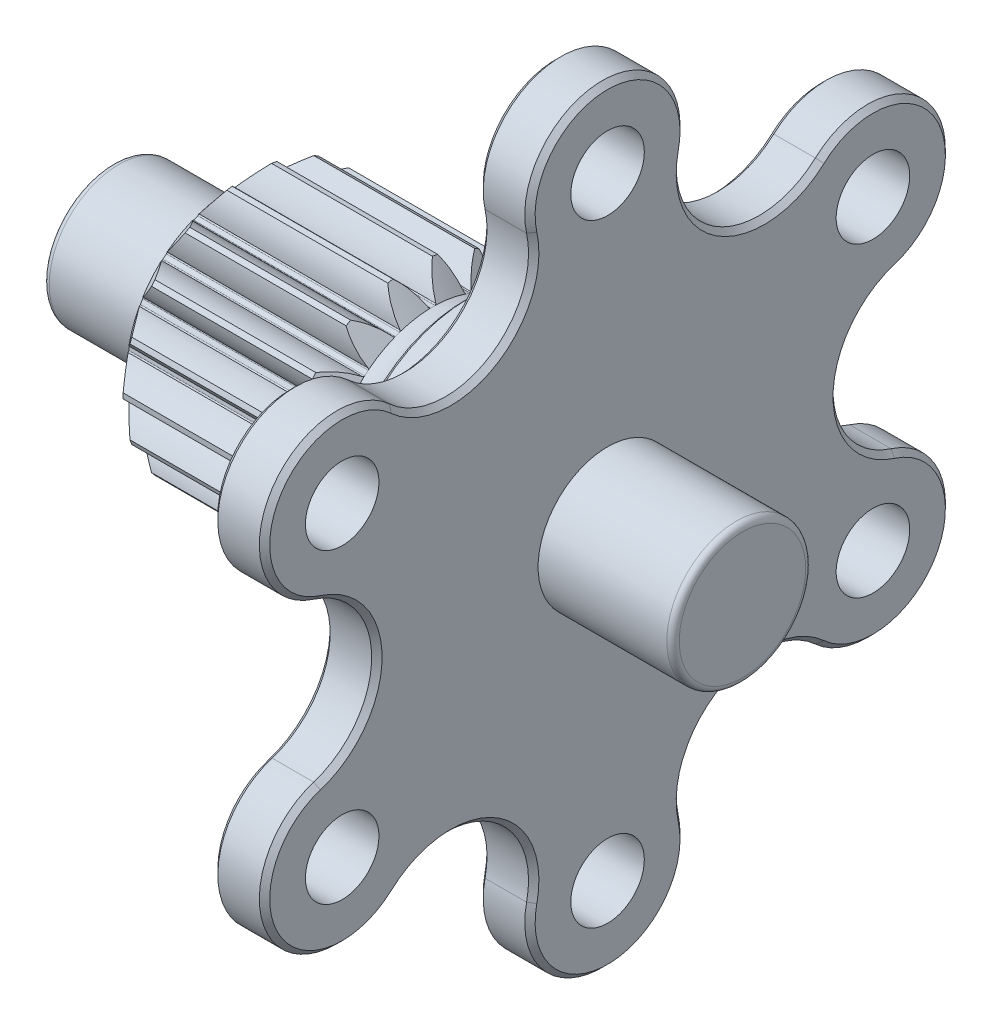
SolidWorks part; units mm, degrees
material "4140 Steel"
ref_plane "X-Y Datum" through (0, 0, 0) normal (0, 0, 1) x (1, 0, 0)
ref_plane "X-Z Datum" through (0, 0, 0) normal (0, 1, 0) x (1, 0, 0)
ref_plane "Y-Z Datum" through (0, 0, 0) normal (1, 0, 0) x (0, 0, -1)
sketch "Sketch1" plane through (0, 0, 0) normal (1, 0, 0) x (0, 0, -1)
  circle A0 centre (0, 0) radius 47
  dimension "D1" = 94
extrude "Base-Extrude" add sketch "Sketch1" against normal blind 6.35
hole_wizard "M8 Clearance Holes" positions "Sketch5" profile "Sketch7" hole size "M8" standard "ANSI Metric" end condition through all
sketch "Sketch5" plane through (0, 0, 0) normal (1, 0, 0) x (0, 0, -1)
  point P0 (0, -37.5)
  dimension "D1" = 37.5
sketch "Sketch7" plane through (0, -37.5, 0) normal (0, 1, 0) x (0, 0, -1)
  line L0 (0, 0) -> (0, 6.35)
  line L1 (0, 6.35) -> (4.5, 6.35)
  line L2 (4.5, 6.35) -> (4.5, 0)
  line L5 (4.5, 0) -> (0, 0)
  line L11 (0, -6.35) -> (0, 107.95) construction
  dimension "Thru Hole Dia." = 9
  dimension "Thru Hole Depth" = 6.35
pattern_circular "CirPattern" count 6 over 360 about axis through (-6.35, 0, 0) along (1, 0, 0) of "M8 Clearance Holes"
sketch "Sketch19" plane through (0, 0, 0) normal (1, 0, 0) x (0, 0, -1)
  line L0 (0, 37.5) -> (32.476, 18.75) construction
  circle A0 centre (0, 37.5) radius 9.5
  circle A1 centre (32.476, 18.75) radius 9.5
  circle A2 centre (0, 0) radius 47 construction
  arc A3 (9.2748, 35.4439) -> (26.0579, 25.7542) centre (19.194, 33.245) ccw
  circle A4 centre (32.476, 18.75) radius 9.5
  circle A5 centre (32.476, -18.75) radius 9.5
  arc A6 (35.3328, 9.6897) -> (35.3328, -9.6897) centre (38.3881, 0) ccw
  circle A7 centre (32.476, -18.75) radius 9.5
  circle A8 centre (0, -37.5) radius 9.5
  arc A9 (26.0579, -25.7542) -> (9.2748, -35.4439) centre (19.194, -33.245) ccw
  circle A10 centre (0, -37.5) radius 9.5
  circle A11 centre (-32.476, -18.75) radius 9.5
  arc A12 (-9.2748, -35.4439) -> (-26.0579, -25.7542) centre (-19.194, -33.245) ccw
  circle A13 centre (-32.476, -18.75) radius 9.5
  circle A14 centre (-32.476, 18.75) radius 9.5
  arc A15 (-35.3328, -9.6897) -> (-35.3328, 9.6897) centre (-38.3881, 0) ccw
  circle A16 centre (-32.476, 18.75) radius 9.5
  circle A17 centre (0, 37.5) radius 9.5
  arc A18 (-26.0579, 25.7542) -> (-9.2748, 35.4439) centre (-19.194, 33.245) ccw
  circle A19 centre (-32.476, 18.75) radius 4.5 construction
  circle M12 centre (0, 0) radius 47
  dimension "D1" = 10.16
  dimension "D2" = 6
extrude "Cut-Extrude" cut sketch "Sketch19" against normal through all both and the other way through all contours A16 A18 A0 M12 | A0 A3 A1 M12 | A13 A15 A14 M12 | A4 A6 A5 M12 | A7 A9 A8 M12 | A10 A12 A11 M12 | L0 A3 region at (0, 34.8675, -20.1307) region at (0, 26.6235, -15.3711) region at (0, 33.8688, 19.5541) region at (0, 0, -39.1083) region at (0, 0, 39.1083) region at (0, -33.8688, 19.5541) region at (0, -33.8688, -19.5541)
chamfer "Chamfer1" distance 0.635 angle 45 12 edges at (-6.35, 0, 28.2281) (-6.35, -23.5, 40.7032) (-6.35, 23.5, 40.7032) (-6.35, -24.4462, 14.114) (-6.35, 24.4462, 14.114) (-6.35, -47, 0) (-6.35, 47, 0) (-6.35, -24.4462, -14.114) (-6.35, -23.5, -40.7032) (-6.35, 0, -28.2281) (-6.35, 23.5, -40.7032) (-6.35, 24.4462, -14.114)
sketch "Sketch8" plane through (-6.35, 0, 0) normal (-1, 0, 0) x (0, 0, 1)
  circle A0 centre (0, 0) radius 15.748
  dimension "D1" = 31.496
extrude "Shaft-Extrude" add sketch "Sketch8" along normal blind 52.582
chamfer "Chamfer3" distance 0.635 angle 45 12 edges at (0, -23.5, 40.7032) (0, 0, 28.2281) (0, -24.4462, 14.114) (0, 23.5, 40.7032) (0, -47, 0) (0, 24.4462, 14.114) (0, -24.4462, -14.114) (0, 47, 0) (0, 24.4462, -14.114) (0, -23.5, -40.7032) (0, 0, -28.2281) (0, 23.5, -40.7032)
chamfer "Shaft Chamfer" distance 1 angle 45 1 edges at (-58.932, 0, 15.748)
sketch "Sketch45" plane through (-58.932, 0, 0) normal (-1, 0, 0) x (0, 0, 1)
  circle A0 centre (0, 0) radius 15.748 construction
  circle A1 centre (0, 0) radius 15.748
  circle A2 centre (0, 0) radius 8.5127
  dimension "D1" = 17.0254
extrude "Cut-Extrude1" cut sketch "Sketch45" against normal blind 12.857
chamfer "Chamfer4" [suppressed] distance 0.254 angle 45
sketch "Sketch51" [suppressed] plane through (-6.35, 0, 0) normal (-1, 0, 0) x (0, 0, 1)
  circle A2 centre (0, 0) radius 13.97
  circle A3 centre (0, 0) radius 13.97
  dimension "D1" = 0
extrude "Boss-Extrude1" [suppressed] add sketch "Sketch51" along normal blind 17.5
sketch "Sketch55" plane through (0, 0, 0) normal (1, 0, 0) x (0, 0, -1)
  circle A0 centre (0, 0) radius 8.5
  dimension "D1" = 17
extrude "Boss-Extrude4" add sketch "Sketch55" along normal blind 16.51
sketch "Sketch56" plane through (-58.932, 0, 0) normal (-1, 0, 0) x (0, 0, 1)
  circle A1 centre (0, 0) radius 8.5127
  circle A4 centre (0, 0) radius 8.5127
  dimension "D1" = 0
extrude "Boss-Extrude5" add sketch "Sketch56" along normal blind 1.643
sketch "Sketch22" [suppressed] plane through (-6.35, 0, 0) normal (-1, 0, 0) x (0, 0, 1)
  circle A0 centre (32.476, 18.75) radius 6.1
  circle A1 centre (32.476, -18.75) radius 6.1
  circle A2 centre (0, -37.5) radius 6.1
  circle A3 centre (0, 37.5) radius 6.1
  circle A4 centre (-32.476, 18.75) radius 6.1
  circle A5 centre (-32.476, -18.75) radius 6.1
  dimension "D1" = 12.2
split line "Split Line1" [suppressed]
split line "Split Line2"
sketch "Sketch22<2>" [suppressed] plane through (-6.35, 0, 0) normal (-1, 0, 0) x (0, 0, 1) same geometry as "Sketch22"
fillet "Fillet4" [suppressed] radius 1.5875
ref_plane "Plane3" [suppressed] through (0, 0, 12.7) normal (0, 0, 1) x (1, 0, 0)
sketch "Sketch48" [suppressed] plane through (0, 0, 12.7) normal (0, 0, 1) x (1, 0, 0)
  line L0 (-46.075, 12.446) -> (-46.075, -12.446) construction
  line L1 (-23.85, 3.175) -> (-46.075, 3.175)
  line L3 (-23.85, -3.175) -> (-46.075, -3.175)
  line L4 (-46.075, 3.175) -> (-46.075, -3.175)
  line L5 (-46.075, 12.446) -> (-46.075, -12.446)
  line L6 (-46.075, 0) -> (-12.2887, 0) construction
  line L7 (-23.85, 12.7) -> (-23.85, -12.7) construction
  arc A0 (-23.85, 3.175) -> (-23.85, -3.175) centre (-23.85, 0) cw
  dimension "D2" = 6.35
extrude "Cut-Extrude3" [suppressed] cut sketch "Sketch48" against normal blind 3.175 and the other way blind 17.5 contours L4 L6 A0 L1 | L6 L5 L3 A0
ref_plane "Plane4" [suppressed] through (0, 0, 13.97) normal (0, 0, 1) x (1, 0, 0)
fillet "Fillet5" [suppressed] radius 0.7937
sketch "Sketch57" [suppressed] plane through (-46.075, 0, 0) normal (-1, 0, 0) x (0, 0, 1)
  arc A0 (9.097, -5.6181) -> (9.7313, -4.4292) centre (0, 0) ccw
  arc A1 (9.097, -5.6181) -> (9.0986, -5.9863) centre (9.3955, -5.8008) ccw
  arc A2 (10.055, -4.164) -> (9.7313, -4.4292) centre (10.071, -4.5136) ccw
  arc A3 (12.1705, -3.6562) -> (12.3682, -3.3733) centre (12.0198, -3.3403) ccw
  arc A4 (12.3682, -3.3733) -> (12.5192, -2.7609) centre (0, 0) ccw
  arc A5 (9.3839, -8.7347) -> (9.8021, -8.2626) centre (0, 0) ccw
  arc A6 (4.2498, -12.0951) -> (4.8395, -11.8715) centre (0, 0) ccw
  arc A7 (-1.8579, -12.6847) -> (-1.2318, -12.7607) centre (0, 0) ccw
  arc A8 (-7.5399, -10.3683) -> (-7.0209, -10.7266) centre (0, 0) ccw
  arc A9 (-11.4947, -5.6767) -> (-11.2016, -6.2352) centre (0, 0) ccw
  arc A10 (-12.82, 0) -> (-12.8161, -0.3154) centre (0, 0) ccw
  arc A11 (12.5274, -2.6855) -> (12.4465, -2.4617) centre (12.1774, -2.6855) ccw
  arc A12 (12.5192, -2.7609) -> (12.5274, -2.6855) centre (12.1774, -2.6855) ccw
  arc A13 (10.6367, -0.7037) -> (10.8093, -1.029) centre (10.986, -0.7268) ccw
  arc A14 (10.6367, -0.7037) -> (10.66, 0) centre (0, 0) ccw
  arc A15 (10.66, 0) -> (10.6367, 0.7037) centre (0, 0) ccw
  arc A16 (10.8093, 1.029) -> (10.6367, 0.7037) centre (10.986, 0.7268) ccw
  arc A17 (12.4465, 2.4617) -> (12.5274, 2.6855) centre (12.1774, 2.6855) ccw
  arc A18 (-12.8161, 0.3154) -> (-12.82, 0) centre (0, 0) ccw
  arc A19 (-11.2016, 6.2352) -> (-11.4947, 5.6767) centre (0, 0) ccw
  arc A20 (-7.0209, 10.7266) -> (-7.5399, 10.3683) centre (0, 0) ccw
  arc A21 (-1.2318, 12.7607) -> (-1.8579, 12.6847) centre (0, 0) ccw
  arc A22 (4.8395, 11.8715) -> (4.2498, 12.0951) centre (0, 0) ccw
  arc A23 (9.8021, 8.2626) -> (9.3839, 8.7347) centre (0, 0) ccw
  arc A24 (12.5192, 2.7609) -> (12.3682, 3.3733) centre (0, 0) ccw
  arc A25 (12.5274, 2.6855) -> (12.5192, 2.7609) centre (12.1774, 2.6855) ccw
  arc A26 (12.3682, 3.3733) -> (12.1649, 3.6044) centre (12.0306, 3.2812) ccw
  arc A27 (9.7454, 4.32) -> (10.0494, 4.1122) centre (10.0654, 4.4619) ccw
  arc A28 (9.7454, 4.32) -> (9.0913, 5.5663) centre (0, 0) ccw
  arc A29 (9.093, 5.9345) -> (9.0913, 5.5663) centre (9.3898, 5.749) ccw
  arc A30 (9.8845, 8.037) -> (9.8021, 8.2626) centre (9.5345, 8.037) ccw
  arc A31 (9.8768, 7.9639) -> (9.8845, 8.037) centre (9.5345, 8.037) ccw
  arc A32 (9.3839, 8.7347) -> (9.0964, 8.8448) centre (9.1277, 8.4962) ccw
  arc A33 (6.6215, 8.3541) -> (5.4632, 9.1536) centre (0, 0) ccw
  arc A34 (6.6215, 8.3541) -> (6.9873, 8.3114) centre (6.8389, 8.6284) ccw
  arc A35 (5.2936, 9.4805) -> (5.4632, 9.1536) centre (5.6426, 9.4542) ccw
  arc A36 (5.0444, 11.6417) -> (4.8395, 11.8715) centre (4.7074, 11.5474) ccw
  arc A37 (4.2498, 12.0951) -> (3.9441, 12.059) centre (4.1338, 11.7649) ccw
  arc A38 (1.9807, 10.4744) -> (0.5835, 10.644) centre (0, 0) ccw
  arc A39 (1.9807, 10.4744) -> (2.3244, 10.6065) centre (2.0458, 10.8183) ccw
  arc A40 (0.2814, 10.8546) -> (0.5835, 10.644) centre (0.6027, 10.9935) ccw
  arc A41 (-0.9435, 12.6525) -> (-1.2318, 12.7607) centre (-1.1981, 12.4123) ccw
  arc A42 (-1.8579, 12.6847) -> (-2.1118, 12.5106) centre (-1.8071, 12.3384) ccw
  arc A43 (-3.1138, 10.1951) -> (-4.4298, 9.696) centre (0, 0) ccw
  arc A44 (-3.1138, 10.1951) -> (-2.8709, 10.4718) centre (-3.2161, 10.5298) ccw
  arc A45 (-4.7952, 9.742) -> (-4.4298, 9.696) centre (-4.5753, 10.0143) ccw
  arc A46 (-6.7154, 10.7647) -> (-7.0209, 10.7266) centre (-6.8292, 10.4338) ccw
  arc A47 (-7.5399, 10.3683) -> (-7.6839, 10.0962) centre (-7.3341, 10.0853) ccw
  arc A48 (-7.4951, 7.5802) -> (-7.3911, 7.8291) centre (-7.7411, 7.8291) ccw
  arc A49 (-7.4951, 7.5802) -> (-8.4284, 6.5267) centre (0, 0) ccw
  arc A50 (-7.3911, 7.8291) -> (-7.4086, 7.9381) centre (-7.7411, 7.8291) ccw
  arc A51 (-8.7733, 6.3977) -> (-8.4284, 6.5267) centre (-8.7051, 6.741) ccw
  arc A52 (-10.9488, 6.4109) -> (-11.2016, 6.2352) centre (-10.8957, 6.065) ccw
  arc A53 (-11.4947, 5.6767) -> (-11.4957, 5.3689) centre (-11.1808, 5.5217) ccw
  arc A54 (-10.1592, 3.2288) -> (-10.4961, 1.8623) centre (0, 0) ccw
  arc A55 (-10.1428, 3.3348) -> (-10.249, 3.5859) centre (-10.4928, 3.3348) ccw
  arc A56 (-10.1592, 3.2288) -> (-10.1428, 3.3348) centre (-10.4928, 3.3348) ccw
  arc A57 (-10.7415, 1.5877) -> (-10.4961, 1.8623) centre (-10.8407, 1.9234) ccw
  arc A58 (-12.674, 0.5884) -> (-12.8161, 0.3154) centre (-12.4662, 0.3067) ccw
  arc A59 (-12.8161, -0.3154) -> (-12.674, -0.5884) centre (-12.4662, -0.3067) ccw
  arc A60 (-10.4961, -1.8623) -> (-10.7415, -1.5877) centre (-10.8407, -1.9234) ccw
  arc A61 (-10.4961, -1.8623) -> (-10.1592, -3.2288) centre (0, 0) ccw
  arc A62 (-10.1428, -3.3348) -> (-10.1592, -3.2288) centre (-10.4928, -3.3348) ccw
  arc A63 (-10.249, -3.5859) -> (-10.1428, -3.3348) centre (-10.4928, -3.3348) ccw
  arc A64 (-11.4957, -5.3689) -> (-11.4947, -5.6767) centre (-11.1808, -5.5217) ccw
  arc A65 (-11.2016, -6.2352) -> (-10.9488, -6.4109) centre (-10.8957, -6.065) ccw
  arc A66 (-8.4284, -6.5267) -> (-8.7733, -6.3977) centre (-8.7051, -6.741) ccw
  arc A67 (-8.4284, -6.5267) -> (-7.4951, -7.5802) centre (0, 0) ccw
  arc A68 (-7.3911, -7.8291) -> (-7.4951, -7.5802) centre (-7.7411, -7.8291) ccw
  arc A69 (-7.4086, -7.9381) -> (-7.3911, -7.8291) centre (-7.7411, -7.8291) ccw
  arc A70 (-7.6839, -10.0962) -> (-7.5399, -10.3683) centre (-7.3341, -10.0853) ccw
  arc A71 (-7.0209, -10.7266) -> (-6.7154, -10.7647) centre (-6.8292, -10.4338) ccw
  arc A72 (-4.4298, -9.696) -> (-4.7952, -9.742) centre (-4.5753, -10.0143) ccw
  arc A73 (-4.4298, -9.696) -> (-3.1138, -10.1951) centre (0, 0) ccw
  arc A74 (-2.8709, -10.4718) -> (-3.1138, -10.1951) centre (-3.2161, -10.5298) ccw
  arc A75 (-2.1118, -12.5106) -> (-1.8579, -12.6847) centre (-1.8071, -12.3384) ccw
  arc A76 (-1.2318, -12.7607) -> (-0.9435, -12.6525) centre (-1.1981, -12.4123) ccw
  arc A77 (0.5835, -10.644) -> (1.9807, -10.4744) centre (0, 0) ccw
  arc A78 (0.5835, -10.644) -> (0.2814, -10.8546) centre (0.6027, -10.9935) ccw
  arc A79 (2.3244, -10.6065) -> (1.9807, -10.4744) centre (2.0458, -10.8183) ccw
  arc A80 (3.9441, -12.059) -> (4.2498, -12.0951) centre (4.1338, -11.7649) ccw
  arc A81 (4.8395, -11.8715) -> (5.0444, -11.6417) centre (4.7074, -11.5474) ccw
  arc A82 (5.4632, -9.1536) -> (5.2936, -9.4805) centre (5.6426, -9.4542) ccw
  arc A83 (5.4632, -9.1536) -> (6.6215, -8.3541) centre (0, 0) ccw
  arc A84 (6.9873, -8.3114) -> (6.6215, -8.3541) centre (6.8389, -8.6284) ccw
  arc A85 (9.0964, -8.8448) -> (9.3839, -8.7347) centre (9.1277, -8.4962) ccw
  arc A86 (9.8021, -8.2626) -> (9.8901, -8.0888) centre (9.5462, -8.0238) ccw
  arc A87 (9.8901, -8.0888) -> (9.8824, -8.0157) centre (9.5401, -8.0888) ccw
  circle A88 centre (0, 0) radius 13.97 construction
  circle A89 centre (0, 0) radius 13.97
  spline S0 degree 4 poles (9.0986, -5.9863) (9.1513, -6.0706) (9.2437, -6.2285) (9.367, -6.4648) (9.5091, -6.7844) (9.6282, -7.0962) (9.741, -7.4422) (9.814, -7.7129) (9.8587, -7.9047) (9.8824, -8.0157) knots 0 0 0 0 0 0.181969 0.334561 0.487154 0.639745 0.792337 1 1 1 1 1 weights 1 1 1 1 1 1 1 1 1 1
  spline S1 degree 4 poles (10.055, -4.164) (10.1544, -4.1595) (10.3368, -4.1458) (10.6013, -4.113) (10.9451, -4.0484) (11.2693, -3.9693) (11.6181, -3.8656) (11.8824, -3.7718) (12.0657, -3.6997) (12.1705, -3.6562) knots 0 0 0 0 0 0.181969 0.334561 0.487154 0.639745 0.792337 1 1 1 1 1 weights 1 1 1 1 1 1 1 1 1 1
  spline S2 degree 4 poles (10.8093, -1.029) (10.8952, -1.0792) (11.0504, -1.176) (11.2693, -1.328) (11.5437, -1.545) (11.7941, -1.7657) (12.0547, -2.0196) (12.2452, -2.2255) (12.3739, -2.3745) (12.4465, -2.4617) knots 0 0 0 0 0 0.181969 0.334561 0.487154 0.639745 0.792337 1 1 1 1 1 weights 1 1 1 1 1 1 1 1 1 1
  spline S3 degree 4 poles (10.8093, 1.029) (10.8952, 1.0792) (11.0504, 1.176) (11.2693, 1.328) (11.5437, 1.545) (11.7941, 1.7657) (12.0547, 2.0196) (12.2452, 2.2255) (12.3739, 2.3745) (12.4465, 2.4617) knots 0 0 0 0 0 0.181969 0.334561 0.487154 0.639745 0.792337 1 1 1 1 1 weights 1 1 1 1 1 1 1 1 1 1
  spline S4 degree 4 poles (10.0494, 4.1122) (10.1488, 4.1077) (10.3312, 4.094) (10.5956, 4.0613) (10.9394, 3.9966) (11.2637, 3.9175) (11.6125, 3.8138) (11.8768, 3.7201) (12.06, 3.648) (12.1649, 3.6044) knots 0 0 0 0 0 0.181969 0.334561 0.487154 0.639745 0.792337 1 1 1 1 1 weights 1 1 1 1 1 1 1 1 1 1
  spline S5 degree 4 poles (9.093, 5.9345) (9.1457, 6.0188) (9.2381, 6.1767) (9.3613, 6.413) (9.5035, 6.7326) (9.6225, 7.0445) (9.7353, 7.3904) (9.8083, 7.6612) (9.8531, 7.8529) (9.8768, 7.9639) knots 0 0 0 0 0 0.181969 0.334561 0.487154 0.639745 0.792337 1 1 1 1 1 weights 1 1 1 1 1 1 1 1 1 1
  spline S6 degree 4 poles (6.9873, 8.3114) (7.0773, 8.3535) (7.2452, 8.4262) (7.4946, 8.5201) (7.8291, 8.6227) (8.153, 8.7033) (8.51, 8.7735) (8.7876, 8.8134) (8.9833, 8.8347) (9.0964, 8.8448) knots 0 0 0 0 0 0.181969 0.334561 0.487154 0.639745 0.792337 1 1 1 1 1 weights 1 1 1 1 1 1 1 1 1 1
  spline S7 degree 4 poles (5.2936, 9.4805) (5.301, 9.5796) (5.3095, 9.7624) (5.3088, 10.0288) (5.2861, 10.3779) (5.2466, 10.7094) (5.1857, 11.0681) (5.1245, 11.3418) (5.075, 11.5324) (5.0444, 11.6417) knots 0 0 0 0 0 0.181969 0.334561 0.487154 0.639745 0.792337 1 1 1 1 1 weights 1 1 1 1 1 1 1 1 1 1
  spline S8 degree 4 poles (2.3244, 10.6065) (2.3846, 10.6857) (2.4995, 10.8281) (2.6767, 11.0271) (2.9252, 11.2733) (3.1745, 11.4952) (3.4579, 11.7234) (3.6852, 11.8876) (3.8487, 11.9975) (3.9441, 12.059) knots 0 0 0 0 0 0.181969 0.334561 0.487154 0.639745 0.792337 1 1 1 1 1 weights 1 1 1 1 1 1 1 1 1 1
  spline S9 degree 4 poles (0.2814, 10.8546) (0.2419, 10.9458) (0.1645, 11.1116) (0.0401, 11.3472) (-0.1423, 11.6458) (-0.3313, 11.9209) (-0.5519, 12.2102) (-0.7332, 12.4241) (-0.8657, 12.5699) (-0.9435, 12.6525) knots 0 0 0 0 0 0.181969 0.334561 0.487154 0.639745 0.792337 1 1 1 1 1 weights 1 1 1 1 1 1 1 1 1 1
  spline S10 degree 4 poles (-2.8709, 10.4718) (-2.8544, 10.5699) (-2.8189, 10.7493) (-2.7545, 11.0079) (-2.6489, 11.3414) (-2.5312, 11.6538) (-2.3863, 11.9875) (-2.2613, 12.2386) (-2.1677, 12.4118) (-2.1118, 12.5106) knots 0 0 0 0 0 0.181969 0.334561 0.487154 0.639745 0.792337 1 1 1 1 1 weights 1 1 1 1 1 1 1 1 1 1
  spline S11 degree 4 poles (-4.7952, 9.742) (-4.8726, 9.8045) (-5.0181, 9.9153) (-5.2378, 10.0661) (-5.538, 10.2457) (-5.8332, 10.4015) (-6.163, 10.5552) (-6.423, 10.6603) (-6.608, 10.7278) (-6.7154, 10.7647) knots 0 0 0 0 0 0.181969 0.334561 0.487154 0.639745 0.792337 1 1 1 1 1 weights 1 1 1 1 1 1 1 1 1 1
  spline S12 degree 4 poles (-7.4086, 7.9381) (-7.4395, 8.0326) (-7.4915, 8.2081) (-7.5546, 8.4669) (-7.6161, 8.8113) (-7.6571, 9.1426) (-7.6838, 9.5054) (-7.6899, 9.7858) (-7.6874, 9.9827) (-7.6839, 10.0962) knots 0 0 0 0 0 0.181969 0.334561 0.487154 0.639745 0.792337 1 1 1 1 1 weights 1 1 1 1 1 1 1 1 1 1
  spline S13 degree 4 poles (-8.7733, 6.3977) (-8.8708, 6.4171) (-9.0512, 6.4475) (-9.3158, 6.4789) (-9.6651, 6.4985) (-9.9989, 6.4992) (-10.3623, 6.482) (-10.6414, 6.4543) (-10.8366, 6.4281) (-10.9488, 6.4109) knots 0 0 0 0 0 0.181969 0.334561 0.487154 0.639745 0.792337 1 1 1 1 1 weights 1 1 1 1 1 1 1 1 1 1
  spline S14 degree 4 poles (-10.249, 3.5859) (-10.3203, 3.6552) (-10.4478, 3.7864) (-10.624, 3.9863) (-10.8386, 4.2627) (-11.0288, 4.5369) (-11.2211, 4.8458) (-11.3567, 5.0913) (-11.4461, 5.2667) (-11.4957, 5.3689) knots 0 0 0 0 0 0.181969 0.334561 0.487154 0.639745 0.792337 1 1 1 1 1 weights 1 1 1 1 1 1 1 1 1 1
  spline S15 degree 4 poles (-10.7415, 1.5877) (-10.8369, 1.5596) (-11.0107, 1.5027) (-11.2597, 1.4075) (-11.578, 1.2625) (-11.8739, 1.1081) (-12.1877, 0.9239) (-12.4219, 0.7697) (-12.5826, 0.6558) (-12.674, 0.5884) knots 0 0 0 0 0 0.181969 0.334561 0.487154 0.639745 0.792337 1 1 1 1 1 weights 1 1 1 1 1 1 1 1 1 1
  spline S16 degree 4 poles (-10.7415, -1.5877) (-10.8369, -1.5596) (-11.0107, -1.5027) (-11.2597, -1.4075) (-11.578, -1.2625) (-11.8739, -1.1081) (-12.1877, -0.9239) (-12.4219, -0.7697) (-12.5826, -0.6558) (-12.674, -0.5884) knots 0 0 0 0 0 0.181969 0.334561 0.487154 0.639745 0.792337 1 1 1 1 1 weights 1 1 1 1 1 1 1 1 1 1
  spline S17 degree 4 poles (-10.249, -3.5859) (-10.3203, -3.6552) (-10.4478, -3.7864) (-10.624, -3.9863) (-10.8386, -4.2627) (-11.0288, -4.5369) (-11.2211, -4.8458) (-11.3567, -5.0913) (-11.4461, -5.2667) (-11.4957, -5.3689) knots 0 0 0 0 0 0.181969 0.334561 0.487154 0.639745 0.792337 1 1 1 1 1 weights 1 1 1 1 1 1 1 1 1 1
  spline S18 degree 4 poles (-8.7733, -6.3977) (-8.8708, -6.4171) (-9.0512, -6.4475) (-9.3158, -6.4789) (-9.6651, -6.4985) (-9.9989, -6.4992) (-10.3623, -6.482) (-10.6414, -6.4543) (-10.8366, -6.4281) (-10.9488, -6.4109) knots 0 0 0 0 0 0.181969 0.334561 0.487154 0.639745 0.792337 1 1 1 1 1 weights 1 1 1 1 1 1 1 1 1 1
  spline S19 degree 4 poles (-7.4086, -7.9381) (-7.4395, -8.0326) (-7.4915, -8.2081) (-7.5546, -8.4669) (-7.6161, -8.8113) (-7.6571, -9.1426) (-7.6838, -9.5054) (-7.6899, -9.7858) (-7.6874, -9.9827) (-7.6839, -10.0962) knots 0 0 0 0 0 0.181969 0.334561 0.487154 0.639745 0.792337 1 1 1 1 1 weights 1 1 1 1 1 1 1 1 1 1
  spline S20 degree 4 poles (-4.7952, -9.742) (-4.8726, -9.8045) (-5.0181, -9.9153) (-5.2378, -10.0661) (-5.538, -10.2457) (-5.8332, -10.4015) (-6.163, -10.5552) (-6.423, -10.6603) (-6.608, -10.7278) (-6.7154, -10.7647) knots 0 0 0 0 0 0.181969 0.334561 0.487154 0.639745 0.792337 1 1 1 1 1 weights 1 1 1 1 1 1 1 1 1 1
  spline S21 degree 4 poles (-2.8709, -10.4718) (-2.8544, -10.5699) (-2.8189, -10.7493) (-2.7545, -11.0079) (-2.6489, -11.3414) (-2.5312, -11.6538) (-2.3863, -11.9875) (-2.2613, -12.2386) (-2.1677, -12.4118) (-2.1118, -12.5106) knots 0 0 0 0 0 0.181969 0.334561 0.487154 0.639745 0.792337 1 1 1 1 1 weights 1 1 1 1 1 1 1 1 1 1
  spline S22 degree 4 poles (0.2814, -10.8546) (0.2419, -10.9458) (0.1645, -11.1116) (0.0401, -11.3472) (-0.1423, -11.6458) (-0.3313, -11.9209) (-0.5519, -12.2102) (-0.7332, -12.4241) (-0.8657, -12.5699) (-0.9435, -12.6525) knots 0 0 0 0 0 0.181969 0.334561 0.487154 0.639745 0.792337 1 1 1 1 1 weights 1 1 1 1 1 1 1 1 1 1
  spline S23 degree 4 poles (2.3244, -10.6065) (2.3846, -10.6857) (2.4995, -10.8281) (2.6767, -11.0271) (2.9252, -11.2733) (3.1745, -11.4952) (3.4579, -11.7234) (3.6852, -11.8876) (3.8487, -11.9975) (3.9441, -12.059) knots 0 0 0 0 0 0.181969 0.334561 0.487154 0.639745 0.792337 1 1 1 1 1 weights 1 1 1 1 1 1 1 1 1 1
  spline S24 degree 4 poles (5.2936, -9.4805) (5.301, -9.5796) (5.3095, -9.7624) (5.3088, -10.0288) (5.2861, -10.3779) (5.2466, -10.7094) (5.1857, -11.0681) (5.1245, -11.3418) (5.075, -11.5324) (5.0444, -11.6417) knots 0 0 0 0 0 0.181969 0.334561 0.487154 0.639745 0.792337 1 1 1 1 1 weights 1 1 1 1 1 1 1 1 1 1
  spline S25 degree 4 poles (6.9873, -8.3114) (7.0773, -8.3535) (7.2452, -8.4262) (7.4946, -8.5201) (7.8291, -8.6227) (8.153, -8.7033) (8.51, -8.7735) (8.7876, -8.8134) (8.9833, -8.8347) (9.0964, -8.8448) knots 0 0 0 0 0 0.181969 0.334561 0.487154 0.639745 0.792337 1 1 1 1 1 weights 1 1 1 1 1 1 1 1 1 1
extrude "Cut-Extrude6" [suppressed] cut sketch "Sketch57" against normal blind 22.225
sketch "Sketch58" [suppressed] plane through (-23.85, 0, 0) normal (-1, 0, 0) x (0, 0, 1)
  circle A0 centre (0, 0) radius 12.7679
  circle A1 centre (0, 0) radius 13.97 construction
  circle A2 centre (0, 0) radius 13.97
extrude "Cut-Extrude7" [suppressed] cut sketch "Sketch58" against normal up to surface (17.5 mm away) up to face at (-6.35, 0, -15.748)
sketch "Sketch59" [suppressed] plane through (-23.85, 0, 0) normal (-1, 0, 0) x (0, 0, 1)
  circle A1 centre (0, 0) radius 12.7679 construction
  circle A2 centre (0, 0) radius 12.7679
  circle A7 centre (0, 0) radius 10.541
  dimension "D1" = 21.082
extrude "Cut-Extrude10" [suppressed] cut sketch "Sketch59" against normal blind 3.175
chamfer "Chamfer5" [suppressed] distance 1.524 angle 45
sketch "Sketch65" [suppressed] plane through (-46.075, 0, 0) normal (-1, 0, 0) x (0, 0, 1)
  arc A3 (9.097, -5.6181) -> (9.0986, -5.9863) centre (9.3955, -5.8008) ccw
  arc A84 (9.097, -5.6181) -> (9.0986, -5.9863) centre (9.3955, -5.8008) ccw
  arc A85 (9.097, -5.6181) -> (9.7313, -4.4292) centre (0, 0) ccw
  arc A86 (9.097, -5.6181) -> (9.7313, -4.4292) centre (0, 0) ccw
  arc A87 (10.055, -4.164) -> (9.7313, -4.4292) centre (10.071, -4.5136) ccw
  arc A88 (10.055, -4.164) -> (9.7313, -4.4292) centre (10.071, -4.5136) ccw
  arc A89 (12.1705, -3.6562) -> (12.3682, -3.3733) centre (12.0198, -3.3403) ccw
  arc A90 (12.1705, -3.6562) -> (12.3682, -3.3733) centre (12.0198, -3.3403) ccw
  arc A91 (12.3682, -3.3733) -> (12.5192, -2.7609) centre (0, 0) ccw
  arc A92 (12.3682, -3.3733) -> (12.5192, -2.7609) centre (0, 0) ccw
  arc A93 (12.5192, -2.7609) -> (12.4465, -2.4617) centre (12.1774, -2.6855) ccw
  arc A94 (12.5192, -2.7609) -> (12.4465, -2.4617) centre (12.1774, -2.6855) ccw
  arc A95 (10.6367, -0.7037) -> (10.8093, -1.029) centre (10.986, -0.7268) ccw
  arc A96 (10.6367, -0.7037) -> (10.8093, -1.029) centre (10.986, -0.7268) ccw
  arc A97 (10.6367, -0.7037) -> (10.6367, 0.7037) centre (0, 0) ccw
  arc A98 (10.6367, -0.7037) -> (10.6367, 0.7037) centre (0, 0) ccw
  arc A99 (10.8093, 1.029) -> (10.6367, 0.7037) centre (10.986, 0.7268) ccw
  arc A100 (10.8093, 1.029) -> (10.6367, 0.7037) centre (10.986, 0.7268) ccw
  arc A101 (12.4465, 2.4617) -> (12.5192, 2.7609) centre (12.1774, 2.6855) ccw
  arc A102 (12.4465, 2.4617) -> (12.5192, 2.7609) centre (12.1774, 2.6855) ccw
  arc A103 (12.5192, 2.7609) -> (12.3682, 3.3733) centre (0, 0) ccw
  arc A104 (12.5192, 2.7609) -> (12.3682, 3.3733) centre (0, 0) ccw
  arc A105 (12.3682, 3.3733) -> (12.1649, 3.6044) centre (12.0306, 3.2812) ccw
  arc A106 (12.3682, 3.3733) -> (12.1649, 3.6044) centre (12.0306, 3.2812) ccw
  arc A107 (9.7454, 4.32) -> (10.0494, 4.1122) centre (10.0654, 4.4619) ccw
  arc A108 (9.7454, 4.32) -> (10.0494, 4.1122) centre (10.0654, 4.4619) ccw
  arc A109 (9.7454, 4.32) -> (9.0913, 5.5663) centre (0, 0) ccw
  arc A110 (9.7454, 4.32) -> (9.0913, 5.5663) centre (0, 0) ccw
  arc A111 (9.093, 5.9345) -> (9.0913, 5.5663) centre (9.3898, 5.749) ccw
  arc A112 (9.093, 5.9345) -> (9.0913, 5.5663) centre (9.3898, 5.749) ccw
  arc A113 (9.8768, 7.9639) -> (9.8021, 8.2626) centre (9.5345, 8.037) ccw
  arc A114 (9.8768, 7.9639) -> (9.8021, 8.2626) centre (9.5345, 8.037) ccw
  arc A115 (9.8021, 8.2626) -> (9.3839, 8.7347) centre (0, 0) ccw
  arc A116 (9.8021, 8.2626) -> (9.3839, 8.7347) centre (0, 0) ccw
  arc A117 (9.3839, 8.7347) -> (9.0964, 8.8448) centre (9.1277, 8.4962) ccw
  arc A118 (9.3839, 8.7347) -> (9.0964, 8.8448) centre (9.1277, 8.4962) ccw
  arc A119 (6.6215, 8.3541) -> (6.9873, 8.3114) centre (6.8389, 8.6284) ccw
  arc A120 (6.6215, 8.3541) -> (6.9873, 8.3114) centre (6.8389, 8.6284) ccw
  arc A121 (6.6215, 8.3541) -> (5.4632, 9.1536) centre (0, 0) ccw
  arc A122 (6.6215, 8.3541) -> (5.4632, 9.1536) centre (0, 0) ccw
  arc A123 (5.2936, 9.4805) -> (5.4632, 9.1536) centre (5.6426, 9.4542) ccw
  arc A124 (5.2936, 9.4805) -> (5.4632, 9.1536) centre (5.6426, 9.4542) ccw
  arc A125 (5.0444, 11.6417) -> (4.8395, 11.8715) centre (4.7074, 11.5474) ccw
  arc A126 (5.0444, 11.6417) -> (4.8395, 11.8715) centre (4.7074, 11.5474) ccw
  arc A127 (4.8395, 11.8715) -> (4.2498, 12.0951) centre (0, 0) ccw
  arc A128 (4.8395, 11.8715) -> (4.2498, 12.0951) centre (0, 0) ccw
  arc A129 (4.2498, 12.0951) -> (3.9441, 12.059) centre (4.1338, 11.7649) ccw
  arc A130 (4.2498, 12.0951) -> (3.9441, 12.059) centre (4.1338, 11.7649) ccw
  arc A131 (1.9807, 10.4744) -> (2.3244, 10.6065) centre (2.0458, 10.8183) ccw
  arc A132 (1.9807, 10.4744) -> (2.3244, 10.6065) centre (2.0458, 10.8183) ccw
  arc A133 (1.9807, 10.4744) -> (0.5835, 10.644) centre (0, 0) ccw
  arc A134 (1.9807, 10.4744) -> (0.5835, 10.644) centre (0, 0) ccw
  arc A135 (0.2814, 10.8546) -> (0.5835, 10.644) centre (0.6027, 10.9935) ccw
  arc A136 (0.2814, 10.8546) -> (0.5835, 10.644) centre (0.6027, 10.9935) ccw
  arc A137 (-0.9435, 12.6525) -> (-1.2318, 12.7607) centre (-1.1981, 12.4123) ccw
  arc A138 (-0.9435, 12.6525) -> (-1.2318, 12.7607) centre (-1.1981, 12.4123) ccw
  arc A139 (-1.2318, 12.7607) -> (-1.8579, 12.6847) centre (0, 0) ccw
  arc A140 (-1.2318, 12.7607) -> (-1.8579, 12.6847) centre (0, 0) ccw
  arc A141 (-1.8579, 12.6847) -> (-2.1118, 12.5106) centre (-1.8071, 12.3384) ccw
  arc A142 (-1.8579, 12.6847) -> (-2.1118, 12.5106) centre (-1.8071, 12.3384) ccw
  arc A143 (-3.1138, 10.1951) -> (-2.8709, 10.4718) centre (-3.2161, 10.5298) ccw
  arc A144 (-3.1138, 10.1951) -> (-2.8709, 10.4718) centre (-3.2161, 10.5298) ccw
  arc A145 (-3.1138, 10.1951) -> (-4.4298, 9.696) centre (0, 0) ccw
  arc A146 (-3.1138, 10.1951) -> (-4.4298, 9.696) centre (0, 0) ccw
  arc A147 (-4.7952, 9.742) -> (-4.4298, 9.696) centre (-4.5753, 10.0143) ccw
  arc A148 (-4.7952, 9.742) -> (-4.4298, 9.696) centre (-4.5753, 10.0143) ccw
  arc A149 (-6.7154, 10.7647) -> (-7.0209, 10.7266) centre (-6.8292, 10.4338) ccw
  arc A150 (-6.7154, 10.7647) -> (-7.0209, 10.7266) centre (-6.8292, 10.4338) ccw
  arc A151 (-7.0209, 10.7266) -> (-7.5399, 10.3683) centre (0, 0) ccw
  arc A152 (-7.0209, 10.7266) -> (-7.5399, 10.3683) centre (0, 0) ccw
  arc A153 (-7.5399, 10.3683) -> (-7.6839, 10.0962) centre (-7.3341, 10.0853) ccw
  arc A154 (-7.5399, 10.3683) -> (-7.6839, 10.0962) centre (-7.3341, 10.0853) ccw
  arc A155 (-7.4951, 7.5802) -> (-7.4086, 7.9381) centre (-7.7411, 7.8291) ccw
  arc A156 (-7.4951, 7.5802) -> (-7.4086, 7.9381) centre (-7.7411, 7.8291) ccw
  arc A157 (-7.4951, 7.5802) -> (-8.4284, 6.5267) centre (0, 0) ccw
  arc A158 (-7.4951, 7.5802) -> (-8.4284, 6.5267) centre (0, 0) ccw
  arc A159 (-8.7733, 6.3977) -> (-8.4284, 6.5267) centre (-8.7051, 6.741) ccw
  arc A160 (-8.7733, 6.3977) -> (-8.4284, 6.5267) centre (-8.7051, 6.741) ccw
  arc A161 (-10.9488, 6.4109) -> (-11.2016, 6.2352) centre (-10.8957, 6.065) ccw
  arc A162 (-10.9488, 6.4109) -> (-11.2016, 6.2352) centre (-10.8957, 6.065) ccw
  arc A163 (-11.2016, 6.2352) -> (-11.4947, 5.6767) centre (0, 0) ccw
  arc A164 (-11.2016, 6.2352) -> (-11.4947, 5.6767) centre (0, 0) ccw
  arc A165 (-11.4947, 5.6767) -> (-11.4957, 5.3689) centre (-11.1808, 5.5217) ccw
  arc A166 (-11.4947, 5.6767) -> (-11.4957, 5.3689) centre (-11.1808, 5.5217) ccw
  arc A167 (-10.1592, 3.2288) -> (-10.249, 3.5859) centre (-10.4928, 3.3348) ccw
  arc A168 (-10.1592, 3.2288) -> (-10.249, 3.5859) centre (-10.4928, 3.3348) ccw
  arc A169 (-10.1592, 3.2288) -> (-10.4961, 1.8623) centre (0, 0) ccw
  arc A170 (-10.1592, 3.2288) -> (-10.4961, 1.8623) centre (0, 0) ccw
  arc A171 (-10.7415, 1.5877) -> (-10.4961, 1.8623) centre (-10.8407, 1.9234) ccw
  arc A172 (-10.7415, 1.5877) -> (-10.4961, 1.8623) centre (-10.8407, 1.9234) ccw
  arc A173 (-12.674, 0.5884) -> (-12.8161, 0.3154) centre (-12.4662, 0.3067) ccw
  arc A174 (-12.674, 0.5884) -> (-12.8161, 0.3154) centre (-12.4662, 0.3067) ccw
  arc A175 (-12.8161, 0.3154) -> (-12.8161, -0.3154) centre (0, 0) ccw
  arc A176 (-12.8161, 0.3154) -> (-12.8161, -0.3154) centre (0, 0) ccw
  arc A177 (-12.8161, -0.3154) -> (-12.674, -0.5884) centre (-12.4662, -0.3067) ccw
  arc A178 (-12.8161, -0.3154) -> (-12.674, -0.5884) centre (-12.4662, -0.3067) ccw
  arc A179 (-10.4961, -1.8623) -> (-10.7415, -1.5877) centre (-10.8407, -1.9234) ccw
  arc A180 (-10.4961, -1.8623) -> (-10.7415, -1.5877) centre (-10.8407, -1.9234) ccw
  arc A181 (-10.4961, -1.8623) -> (-10.1592, -3.2288) centre (0, 0) ccw
  arc A182 (-10.4961, -1.8623) -> (-10.1592, -3.2288) centre (0, 0) ccw
  arc A183 (-10.249, -3.5859) -> (-10.1592, -3.2288) centre (-10.4928, -3.3348) ccw
  arc A184 (-10.249, -3.5859) -> (-10.1592, -3.2288) centre (-10.4928, -3.3348) ccw
  arc A185 (-11.4957, -5.3689) -> (-11.4947, -5.6767) centre (-11.1808, -5.5217) ccw
  arc A186 (-11.4957, -5.3689) -> (-11.4947, -5.6767) centre (-11.1808, -5.5217) ccw
  arc A187 (-11.4947, -5.6767) -> (-11.2016, -6.2352) centre (0, 0) ccw
  arc A188 (-11.4947, -5.6767) -> (-11.2016, -6.2352) centre (0, 0) ccw
  arc A189 (-11.2016, -6.2352) -> (-10.9488, -6.4109) centre (-10.8957, -6.065) ccw
  arc A190 (-11.2016, -6.2352) -> (-10.9488, -6.4109) centre (-10.8957, -6.065) ccw
  arc A191 (-8.4284, -6.5267) -> (-8.7733, -6.3977) centre (-8.7051, -6.741) ccw
  arc A192 (-8.4284, -6.5267) -> (-8.7733, -6.3977) centre (-8.7051, -6.741) ccw
  arc A193 (-8.4284, -6.5267) -> (-7.4951, -7.5802) centre (0, 0) ccw
  arc A194 (-8.4284, -6.5267) -> (-7.4951, -7.5802) centre (0, 0) ccw
  arc A195 (-7.4086, -7.9381) -> (-7.4951, -7.5802) centre (-7.7411, -7.8291) ccw
  arc A196 (-7.4086, -7.9381) -> (-7.4951, -7.5802) centre (-7.7411, -7.8291) ccw
  arc A197 (-7.6839, -10.0962) -> (-7.5399, -10.3683) centre (-7.3341, -10.0853) ccw
  arc A198 (-7.6839, -10.0962) -> (-7.5399, -10.3683) centre (-7.3341, -10.0853) ccw
  arc A199 (-7.5399, -10.3683) -> (-7.0209, -10.7266) centre (0, 0) ccw
  arc A200 (-7.5399, -10.3683) -> (-7.0209, -10.7266) centre (0, 0) ccw
  arc A201 (-7.0209, -10.7266) -> (-6.7154, -10.7647) centre (-6.8292, -10.4338) ccw
  arc A202 (-7.0209, -10.7266) -> (-6.7154, -10.7647) centre (-6.8292, -10.4338) ccw
  arc A203 (-4.4298, -9.696) -> (-4.7952, -9.742) centre (-4.5753, -10.0143) ccw
  arc A204 (-4.4298, -9.696) -> (-4.7952, -9.742) centre (-4.5753, -10.0143) ccw
  arc A205 (-4.4298, -9.696) -> (-3.1138, -10.1951) centre (0, 0) ccw
  arc A206 (-4.4298, -9.696) -> (-3.1138, -10.1951) centre (0, 0) ccw
  arc A207 (-2.8709, -10.4718) -> (-3.1138, -10.1951) centre (-3.2161, -10.5298) ccw
  arc A208 (-2.8709, -10.4718) -> (-3.1138, -10.1951) centre (-3.2161, -10.5298) ccw
  arc A209 (-2.1118, -12.5106) -> (-1.8579, -12.6847) centre (-1.8071, -12.3384) ccw
  arc A210 (-2.1118, -12.5106) -> (-1.8579, -12.6847) centre (-1.8071, -12.3384) ccw
  arc A211 (-1.8579, -12.6847) -> (-1.2318, -12.7607) centre (0, 0) ccw
  arc A212 (-1.8579, -12.6847) -> (-1.2318, -12.7607) centre (0, 0) ccw
  arc A213 (-1.2318, -12.7607) -> (-0.9435, -12.6525) centre (-1.1981, -12.4123) ccw
  arc A214 (-1.2318, -12.7607) -> (-0.9435, -12.6525) centre (-1.1981, -12.4123) ccw
  arc A215 (0.5835, -10.644) -> (0.2814, -10.8546) centre (0.6027, -10.9935) ccw
  arc A216 (0.5835, -10.644) -> (0.2814, -10.8546) centre (0.6027, -10.9935) ccw
  arc A217 (0.5835, -10.644) -> (1.9807, -10.4744) centre (0, 0) ccw
  arc A218 (0.5835, -10.644) -> (1.9807, -10.4744) centre (0, 0) ccw
  arc A219 (2.3244, -10.6065) -> (1.9807, -10.4744) centre (2.0458, -10.8183) ccw
  arc A220 (2.3244, -10.6065) -> (1.9807, -10.4744) centre (2.0458, -10.8183) ccw
  arc A221 (3.9441, -12.059) -> (4.2498, -12.0951) centre (4.1338, -11.7649) ccw
  arc A222 (3.9441, -12.059) -> (4.2498, -12.0951) centre (4.1338, -11.7649) ccw
  arc A223 (4.2498, -12.0951) -> (4.8395, -11.8715) centre (0, 0) ccw
  arc A224 (4.2498, -12.0951) -> (4.8395, -11.8715) centre (0, 0) ccw
  arc A225 (4.8395, -11.8715) -> (5.0444, -11.6417) centre (4.7074, -11.5474) ccw
  arc A226 (4.8395, -11.8715) -> (5.0444, -11.6417) centre (4.7074, -11.5474) ccw
  arc A227 (5.4632, -9.1536) -> (5.2936, -9.4805) centre (5.6426, -9.4542) ccw
  arc A228 (5.4632, -9.1536) -> (5.2936, -9.4805) centre (5.6426, -9.4542) ccw
  arc A229 (5.4632, -9.1536) -> (6.6215, -8.3541) centre (0, 0) ccw
  arc A230 (5.4632, -9.1536) -> (6.6215, -8.3541) centre (0, 0) ccw
  arc A231 (6.9873, -8.3114) -> (6.6215, -8.3541) centre (6.8389, -8.6284) ccw
  arc A232 (6.9873, -8.3114) -> (6.6215, -8.3541) centre (6.8389, -8.6284) ccw
  arc A233 (9.0964, -8.8448) -> (9.3839, -8.7347) centre (9.1277, -8.4962) ccw
  arc A234 (9.0964, -8.8448) -> (9.3839, -8.7347) centre (9.1277, -8.4962) ccw
  arc A235 (9.3839, -8.7347) -> (9.8021, -8.2626) centre (0, 0) ccw
  arc A236 (9.3839, -8.7347) -> (9.8021, -8.2626) centre (0, 0) ccw
  arc A237 (9.8021, -8.2626) -> (9.8901, -8.0888) centre (9.5462, -8.0238) ccw
  arc A238 (9.8021, -8.2626) -> (9.8901, -8.0888) centre (9.5462, -8.0238) ccw
  arc A239 (9.8901, -8.0888) -> (9.8824, -8.0157) centre (9.5401, -8.0888) ccw
  arc A240 (9.8901, -8.0888) -> (9.8824, -8.0157) centre (9.5401, -8.0888) ccw
  spline S26 degree 4 poles (-1532.433, -2581.0456) (28.0386, 43.5406) (-7.8065, -37.1034) (13.3189, -18.4144) (9.6282, -7.0962) (9.5091, -6.7844) (6.3236, 0.3799) (-9.5593, 1.4) (-87.6696, -77.5479) (-1631.3956, -2516.9623) knots -21.107174 -21.107174 -21.107174 -21.107174 -21.107174 0.207663 0.360255 0.512846 0.665439 0.818031 14.698211 14.698211 14.698211 14.698211 14.698211 weights 1 1 1 1 1 1 1 1 1 1 only from (9.8824, -8.0157) to (9.0986, -5.9863)
  spline S27 degree 4 poles (9.8824, -8.0157) (9.8587, -7.9047) (9.814, -7.7129) (9.741, -7.4422) (9.6282, -7.0962) (9.5091, -6.7844) (9.367, -6.4648) (9.2437, -6.2285) (9.1513, -6.0706) (9.0986, -5.9863) knots 0 0 0 0 0 0.207663 0.360255 0.512846 0.665439 0.818031 1 1 1 1 1 weights 1 1 1 1 1 1 1 1 1 1
  spline S28 degree 4 poles (1144.6493, 2772.3531) (13.9786, 116.1269) (-6.6227, 6.9953) (3.2393, -5.4966) (10.9451, -4.0484) (11.2693, -3.9693) (22.6805, -0.5773) (26.0607, 27.4252) (-19.9456, -47.8857) (1253.5971, 2727.2911) knots -13.698237 -13.698237 -13.698237 -13.698237 -13.698237 0.181969 0.334561 0.487154 0.639745 0.792337 22.107172 22.107172 22.107172 22.107172 22.107172 weights 1 1 1 1 1 1 1 1 1 1 only from (10.055, -4.164) to (12.1705, -3.6562)
  spline S29 degree 4 poles (10.055, -4.164) (10.1544, -4.1595) (10.3368, -4.1458) (10.6013, -4.113) (10.9451, -4.0484) (11.2693, -3.9693) (11.6181, -3.8656) (11.8824, -3.7718) (12.0657, -3.6997) (12.1705, -3.6562) knots 0 0 0 0 0 0.181969 0.334561 0.487154 0.639745 0.792337 1 1 1 1 1 weights 1 1 1 1 1 1 1 1 1 1
  spline S30 degree 4 poles (-157.4594, -2997.5162) (4.5636, 51.6267) (10.3014, -36.4381) (20.3218, -10.0723) (11.7941, -1.7657) (11.5437, -1.545) (5.3937, 3.3184) (-9.144, -3.1595) (-41.6183, -109.3641) (-274.8674, -2986.7636) knots -21.107174 -21.107174 -21.107174 -21.107174 -21.107174 0.207663 0.360255 0.512846 0.665439 0.818031 14.698211 14.698211 14.698211 14.698211 14.698211 weights 1 1 1 1 1 1 1 1 1 1 only from (12.4465, -2.4617) to (10.8093, -1.029)
  spline S31 degree 4 poles (12.4465, -2.4617) (12.3739, -2.3745) (12.2452, -2.2255) (12.0547, -2.0196) (11.7941, -1.7657) (11.5437, -1.545) (11.2693, -1.328) (11.0504, -1.176) (10.8952, -1.0792) (10.8093, -1.029) knots 0 0 0 0 0 0.207663 0.360255 0.512846 0.665439 0.818031 1 1 1 1 1 weights 1 1 1 1 1 1 1 1 1 1
  spline S32 degree 4 poles (-274.8691, 2986.785) (-41.6185, 109.3647) (-9.144, 3.1596) (5.3936, -3.3184) (11.5437, 1.545) (11.7941, 1.7657) (20.3218, 10.0723) (10.3014, 36.4381) (4.5636, -51.6267) (-157.4594, 2997.5151) knots -13.698237 -13.698237 -13.698237 -13.698237 -13.698237 0.181969 0.334561 0.487154 0.639745 0.792337 22.107172 22.107172 22.107172 22.107172 22.107172 weights 1 1 1 1 1 1 1 1 1 1 only from (10.8093, 1.029) to (12.4465, 2.4617)
  spline S33 degree 4 poles (10.8093, 1.029) (10.8952, 1.0792) (11.0504, 1.176) (11.2693, 1.328) (11.5437, 1.545) (11.7941, 1.7657) (12.0547, 2.0196) (12.2452, 2.2255) (12.3739, 2.3745) (12.4465, 2.4617) knots 0 0 0 0 0 0.181969 0.334561 0.487154 0.639745 0.792337 1 1 1 1 1 weights 1 1 1 1 1 1 1 1 1 1
  spline S34 degree 4 poles (1253.5918, -2727.3439) (-19.9513, 47.834) (26.0551, -27.477) (22.6749, 0.5255) (11.2637, 3.9175) (10.9394, 3.9966) (3.2337, 5.4448) (-6.6283, -7.0471) (13.9728, -116.1781) (1144.6353, -2772.385) knots -21.107174 -21.107174 -21.107174 -21.107174 -21.107174 0.207663 0.360255 0.512846 0.665439 0.818031 14.698211 14.698211 14.698211 14.698211 14.698211 weights 1 1 1 1 1 1 1 1 1 1 only from (12.1649, 3.6044) to (10.0494, 4.1122)
  spline S35 degree 4 poles (12.1649, 3.6044) (12.06, 3.648) (11.8768, 3.7201) (11.6125, 3.8138) (11.2637, 3.9175) (10.9394, 3.9966) (10.5956, 4.0613) (10.3312, 4.094) (10.1488, 4.1077) (10.0494, 4.1122) knots 0 0 0 0 0 0.207663 0.360255 0.512846 0.665439 0.818031 1 1 1 1 1 weights 1 1 1 1 1 1 1 1 1 1
  spline S36 degree 4 poles (-1631.4127, 2516.9288) (-87.6757, 77.4965) (-9.565, -1.4518) (6.318, -0.4317) (9.5035, 6.7326) (9.6225, 7.0445) (13.3133, 18.3626) (-7.8121, 37.0516) (28.033, -43.5924) (-1532.4381, 2580.9928) knots -13.698237 -13.698237 -13.698237 -13.698237 -13.698237 0.181969 0.334561 0.487154 0.639745 0.792337 22.107172 22.107172 22.107172 22.107172 22.107172 weights 1 1 1 1 1 1 1 1 1 1 only from (9.093, 5.9345) to (9.8768, 7.9639)
  spline S37 degree 4 poles (9.093, 5.9345) (9.1457, 6.0188) (9.2381, 6.1767) (9.3613, 6.413) (9.5035, 6.7326) (9.6225, 7.0445) (9.7353, 7.3904) (9.8083, 7.6612) (9.8531, 7.8529) (9.8768, 7.9639) knots 0 0 0 0 0 0.181969 0.334561 0.487154 0.639745 0.792337 1 1 1 1 1 weights 1 1 1 1 1 1 1 1 1 1
  spline S38 degree 4 poles (2377.4603, -1832.3699) (-39.8955, 33.0831) (35.8398, -12.2213) (19.8334, 11.0028) (8.153, 8.7033) (7.8291, 8.6227) (0.333, 6.324) (-2.5941, -9.3202) (66.363, -96.3771) (2301.9158, -1922.8865) knots -21.107174 -21.107174 -21.107174 -21.107174 -21.107174 0.207663 0.360255 0.512846 0.665439 0.818031 14.698211 14.698211 14.698211 14.698211 14.698211 weights 1 1 1 1 1 1 1 1 1 1 only from (9.0964, 8.8448) to (6.9873, 8.3114)
  spline S39 degree 4 poles (9.0964, 8.8448) (8.9833, 8.8347) (8.7876, 8.8134) (8.51, 8.7735) (8.153, 8.7033) (7.8291, 8.6227) (7.4946, 8.5201) (7.2452, 8.4262) (7.0773, 8.3535) (6.9873, 8.3114) knots 0 0 0 0 0 0.207663 0.360255 0.512846 0.665439 0.818031 1 1 1 1 1 weights 1 1 1 1 1 1 1 1 1 1
  spline S40 degree 4 poles (-2614.2193, 1470.4744) (-113.6474, 27.8749) (-7.7947, -5.7306) (5.7949, 2.5538) (5.2861, 10.3779) (5.2466, 10.7094) (3.2548, 22.4462) (-24.136, 29.1771) (45.0803, -25.5716) (-2556.3537, 1573.1961) knots -13.698237 -13.698237 -13.698237 -13.698237 -13.698237 0.181969 0.334561 0.487154 0.639745 0.792337 22.107172 22.107172 22.107172 22.107172 22.107172 weights 1 1 1 1 1 1 1 1 1 1 only from (5.2936, 9.4805) to (5.0444, 11.6417)
  spline S41 degree 4 poles (5.2936, 9.4805) (5.301, 9.5796) (5.3095, 9.7624) (5.3088, 10.0288) (5.2861, 10.3779) (5.2466, 10.7094) (5.1857, 11.0681) (5.1245, 11.3418) (5.075, 11.5324) (5.0444, 11.6417) knots 0 0 0 0 0 0.181969 0.334561 0.487154 0.639745 0.792337 1 1 1 1 1 weights 1 1 1 1 1 1 1 1 1 1
  spline S42 degree 4 poles (2956.6813, -517.622) (-50.7002, 10.7532) (37.4141, 5.8342) (12.4484, 18.9596) (3.1745, 11.4952) (2.9252, 11.2733) (-2.6441, 5.7543) (2.0343, -9.4582) (103.5502, -54.4973) (2931.8551, -632.8779) knots -21.107174 -21.107174 -21.107174 -21.107174 -21.107174 0.207663 0.360255 0.512846 0.665439 0.818031 14.698211 14.698211 14.698211 14.698211 14.698211 weights 1 1 1 1 1 1 1 1 1 1 only from (3.9441, 12.059) to (2.3244, 10.6065)
  spline S43 degree 4 poles (3.9441, 12.059) (3.8487, 11.9975) (3.6852, 11.8876) (3.4579, 11.7234) (3.1745, 11.4952) (2.9252, 11.2733) (2.6767, 11.0271) (2.4995, 10.8281) (2.3846, 10.6857) (2.3244, 10.6065) knots 0 0 0 0 0 0.207663 0.360255 0.512846 0.665439 0.818031 1 1 1 1 1 weights 1 1 1 1 1 1 1 1 1 1
  spline S44 degree 4 poles (-2998.1398, 87.1521) (-113.5839, -28.1326) (-4.2387, -8.6965) (3.9443, 4.9543) (-0.1423, 11.6458) (-0.3313, 11.9209) (-7.5493, 21.3877) (-34.9307, 14.6184) (51.8003, -1.6926) (-2994.6395, 204.9992) knots -13.698237 -13.698237 -13.698237 -13.698237 -13.698237 0.181969 0.334561 0.487154 0.639745 0.792337 22.107172 22.107172 22.107172 22.107172 22.107172 weights 1 1 1 1 1 1 1 1 1 1 only from (0.2814, 10.8546) to (-0.9435, 12.6525)
  spline S45 degree 4 poles (0.2814, 10.8546) (0.2419, 10.9458) (0.1645, 11.1116) (0.0401, 11.3472) (-0.1423, 11.6458) (-0.3313, 11.9209) (-0.5519, 12.2102) (-0.7332, 12.4241) (-0.8657, 12.5699) (-0.9435, 12.6525) knots 0 0 0 0 0 0.181969 0.334561 0.487154 0.639745 0.792337 1 1 1 1 1 weights 1 1 1 1 1 1 1 1 1 1
  spline S46 degree 4 poles (2858.5622, 915.7068) (-49.8901, -14.0401) (30.4172, 22.5531) (2.2115, 22.5729) (-2.5312, 11.6538) (-2.6489, 11.3414) (-5.0154, 3.8664) (6.1967, -7.4294) (117.0153, -0.1328) (2890.1418, 802.1155) knots -21.107174 -21.107174 -21.107174 -21.107174 -21.107174 0.207663 0.360255 0.512846 0.665439 0.818031 14.698211 14.698211 14.698211 14.698211 14.698211 weights 1 1 1 1 1 1 1 1 1 1 only from (-2.1118, 12.5106) to (-2.8709, 10.4718)
  spline S47 degree 4 poles (-2.1118, 12.5106) (-2.1677, 12.4118) (-2.2613, 12.2386) (-2.3863, 11.9875) (-2.5312, 11.6538) (-2.6489, 11.3414) (-2.7545, 11.0079) (-2.8189, 10.7493) (-2.8544, 10.5699) (-2.8709, 10.4718) knots 0 0 0 0 0 0.207663 0.360255 0.512846 0.665439 0.818031 1 1 1 1 1 weights 1 1 1 1 1 1 1 1 1 1
  spline S48 degree 4 poles (-2695.2226, -1316.1357) (-87.4996, -77.6952) (0.2883, -9.6702) (1.1901, 6.2199) (-5.538, 10.2457) (-5.8332, 10.4015) (-16.6239, 15.4295) (-37.7231, -3.2891) (46.6535, 22.5741) (-2746.8895, -1210.1606) knots -13.698237 -13.698237 -13.698237 -13.698237 -13.698237 0.181969 0.334561 0.487154 0.639745 0.792337 22.107172 22.107172 22.107172 22.107172 22.107172 weights 1 1 1 1 1 1 1 1 1 1 only from (-4.7952, 9.742) to (-6.7154, 10.7647)
  spline S49 degree 4 poles (-4.7952, 9.742) (-4.8726, 9.8045) (-5.0181, 9.9153) (-5.2378, 10.0661) (-5.538, 10.2457) (-5.8332, 10.4015) (-6.163, 10.5552) (-6.423, 10.6603) (-6.608, 10.7278) (-6.7154, 10.7647) knots 0 0 0 0 0 0.181969 0.334561 0.487154 0.639745 0.792337 1 1 1 1 1 weights 1 1 1 1 1 1 1 1 1 1
  spline S50 degree 4 poles (2105.581, 2139.2582) (-37.6507, -35.6169) (16.4522, 34.1054) (-8.5319, 21.0151) (-7.6571, 9.1426) (-7.6161, 8.8113) (-6.2377, 1.0928) (8.9395, -3.6986) (103.6736, 54.2622) (2186.3318, 2053.3539) knots -21.107174 -21.107174 -21.107174 -21.107174 -21.107174 0.207663 0.360255 0.512846 0.665439 0.818031 14.698211 14.698211 14.698211 14.698211 14.698211 weights 1 1 1 1 1 1 1 1 1 1 only from (-7.6839, 10.0962) to (-7.4086, 7.9381)
  spline S51 degree 4 poles (-7.6839, 10.0962) (-7.6874, 9.9827) (-7.6899, 9.7858) (-7.6838, 9.5054) (-7.6571, 9.1426) (-7.6161, 8.8113) (-7.5546, 8.4669) (-7.4915, 8.2081) (-7.4395, 8.0326) (-7.4086, 7.9381) knots 0 0 0 0 0 0.207663 0.360255 0.512846 0.665439 0.818031 1 1 1 1 1 weights 1 1 1 1 1 1 1 1 1 1
  spline S52 degree 4 poles (-1774.8623, -2417.9126) (-41.3703, -109.4588) (4.7492, -8.4286) (-1.8367, 6.0605) (-9.6651, 6.4985) (-9.9989, 6.4992) (-21.8902, 5.9367) (-31.8736, -20.4432) (30.8189, 41.6693) (-1869.8602, -2348.0872) knots -13.698237 -13.698237 -13.698237 -13.698237 -13.698237 0.181969 0.334561 0.487154 0.639745 0.792337 22.107172 22.107172 22.107172 22.107172 22.107172 weights 1 1 1 1 1 1 1 1 1 1 only from (-8.7733, 6.3977) to (-10.9488, 6.4109)
  spline S53 degree 4 poles (-8.7733, 6.3977) (-8.8708, 6.4171) (-9.0512, 6.4475) (-9.3158, 6.4789) (-9.6651, 6.4985) (-9.9989, 6.4992) (-10.3623, 6.482) (-10.6414, 6.4543) (-10.8366, 6.4281) (-10.9488, 6.4109) knots 0 0 0 0 0 0.181969 0.334561 0.487154 0.639745 0.792337 1 1 1 1 1 weights 1 1 1 1 1 1 1 1 1 1
  spline S54 degree 4 poles (870.2366, 2872.7314) (-16.786, -49.0344) (-1.2819, 37.8445) (-17.3208, 14.6429) (-11.0288, 4.5369) (-10.8386, 4.2627) (-6.0311, -1.9312) (9.6344, 0.8794) (66.5815, 96.2263) (981.6595, 2834.1936) knots -21.107174 -21.107174 -21.107174 -21.107174 -21.107174 0.207663 0.360255 0.512846 0.665439 0.818031 14.698211 14.698211 14.698211 14.698211 14.698211 weights 1 1 1 1 1 1 1 1 1 1 only from (-11.4957, 5.3689) to (-10.249, 3.5859)
  spline S55 degree 4 poles (-11.4957, 5.3689) (-11.4461, 5.2667) (-11.3567, 5.0913) (-11.2211, 4.8458) (-11.0288, 4.5369) (-10.8386, 4.2627) (-10.624, 3.9863) (-10.4478, 3.7864) (-10.3203, 3.6552) (-10.249, 3.5859) knots 0 0 0 0 0 0.207663 0.360255 0.512846 0.665439 0.818031 1 1 1 1 1 weights 1 1 1 1 1 1 1 1 1 1
  spline S56 degree 4 poles (-447.9025, -2965.775) (14.2365, -116.1467) (8.1222, -5.2561) (-4.4428, 4.5128) (-11.578, 1.2625) (-11.8739, 1.1081) (-22.1417, -4.9163) (-18.7223, -32.9139) (7.9241, 51.2186) (-564.4685, -2948.0953) knots -13.698237 -13.698237 -13.698237 -13.698237 -13.698237 0.181969 0.334561 0.487154 0.639745 0.792337 22.107172 22.107172 22.107172 22.107172 22.107172 weights 1 1 1 1 1 1 1 1 1 1 only from (-10.7415, 1.5877) to (-12.674, 0.5884)
  spline S57 degree 4 poles (-10.7415, 1.5877) (-10.8369, 1.5596) (-11.0107, 1.5027) (-11.2597, 1.4075) (-11.578, 1.2625) (-11.8739, 1.1081) (-12.1877, 0.9239) (-12.4219, 0.7697) (-12.5826, 0.6558) (-12.674, 0.5884) knots 0 0 0 0 0 0.181969 0.334561 0.487154 0.639745 0.792337 1 1 1 1 1 weights 1 1 1 1 1 1 1 1 1 1
  spline S58 degree 4 poles (-564.4687, 2948.0964) (7.9241, -51.2187) (-18.7223, 32.9139) (-22.1417, 4.9163) (-11.8739, -1.1081) (-11.578, -1.2625) (-4.4428, -4.5128) (8.1222, 5.256) (14.2364, 116.1461) (-447.8991, 2965.7537) knots -21.107174 -21.107174 -21.107174 -21.107174 -21.107174 0.207663 0.360255 0.512846 0.665439 0.818031 14.698211 14.698211 14.698211 14.698211 14.698211 weights 1 1 1 1 1 1 1 1 1 1 only from (-12.674, -0.5884) to (-10.7415, -1.5877)
  spline S59 degree 4 poles (-12.674, -0.5884) (-12.5826, -0.6558) (-12.4219, -0.7697) (-12.1877, -0.9239) (-11.8739, -1.1081) (-11.578, -1.2625) (-11.2597, -1.4075) (-11.0107, -1.5027) (-10.8369, -1.5596) (-10.7415, -1.5877) knots 0 0 0 0 0 0.207663 0.360255 0.512846 0.665439 0.818031 1 1 1 1 1 weights 1 1 1 1 1 1 1 1 1 1
  spline S60 degree 4 poles (981.6663, -2834.214) (66.5818, -96.2268) (9.6345, -0.8794) (-6.0311, 1.9312) (-10.8386, -4.2627) (-11.0288, -4.5369) (-17.3208, -14.6429) (-1.2819, -37.8445) (-16.786, 49.0344) (870.2362, -2872.7303) knots -13.698237 -13.698237 -13.698237 -13.698237 -13.698237 0.181969 0.334561 0.487154 0.639745 0.792337 22.107172 22.107172 22.107172 22.107172 22.107172 weights 1 1 1 1 1 1 1 1 1 1 only from (-10.249, -3.5859) to (-11.4957, -5.3689)
  spline S61 degree 4 poles (-10.249, -3.5859) (-10.3203, -3.6552) (-10.4478, -3.7864) (-10.624, -3.9863) (-10.8386, -4.2627) (-11.0288, -4.5369) (-11.2211, -4.8458) (-11.3567, -5.0913) (-11.4461, -5.2667) (-11.4957, -5.3689) knots 0 0 0 0 0 0.181969 0.334561 0.487154 0.639745 0.792337 1 1 1 1 1 weights 1 1 1 1 1 1 1 1 1 1
  spline S62 degree 4 poles (-1869.8609, 2348.088) (30.819, -41.6694) (-31.8736, 20.4432) (-21.8902, -5.9367) (-9.9989, -6.4992) (-9.6651, -6.4985) (-1.8367, -6.0605) (4.7492, 8.4285) (-41.37, 109.4583) (-1774.8494, 2417.8954) knots -21.107174 -21.107174 -21.107174 -21.107174 -21.107174 0.207663 0.360255 0.512846 0.665439 0.818031 14.698211 14.698211 14.698211 14.698211 14.698211 weights 1 1 1 1 1 1 1 1 1 1 only from (-10.9488, -6.4109) to (-8.7733, -6.3977)
  spline S63 degree 4 poles (-10.9488, -6.4109) (-10.8366, -6.4281) (-10.6414, -6.4543) (-10.3623, -6.482) (-9.9989, -6.4992) (-9.6651, -6.4985) (-9.3158, -6.4789) (-9.0512, -6.4475) (-8.8708, -6.4171) (-8.7733, -6.3977) knots 0 0 0 0 0 0.207663 0.360255 0.512846 0.665439 0.818031 1 1 1 1 1 weights 1 1 1 1 1 1 1 1 1 1
  spline S64 degree 4 poles (2186.3473, -2053.3687) (103.6741, -54.2625) (8.9396, 3.6987) (-6.2377, -1.0928) (-7.6161, -8.8113) (-7.6571, -9.1426) (-8.5319, -21.0151) (16.4522, -34.1054) (-37.6507, 35.6169) (2105.5803, -2139.2574) knots -13.698237 -13.698237 -13.698237 -13.698237 -13.698237 0.181969 0.334561 0.487154 0.639745 0.792337 22.107172 22.107172 22.107172 22.107172 22.107172 weights 1 1 1 1 1 1 1 1 1 1 only from (-7.4086, -7.9381) to (-7.6839, -10.0962)
  spline S65 degree 4 poles (-7.4086, -7.9381) (-7.4395, -8.0326) (-7.4915, -8.2081) (-7.5546, -8.4669) (-7.6161, -8.8113) (-7.6571, -9.1426) (-7.6838, -9.5054) (-7.6899, -9.7858) (-7.6874, -9.9827) (-7.6839, -10.0962) knots 0 0 0 0 0 0.181969 0.334561 0.487154 0.639745 0.792337 1 1 1 1 1 weights 1 1 1 1 1 1 1 1 1 1
  spline S66 degree 4 poles (-2746.8905, 1210.161) (46.6535, -22.5741) (-37.7231, 3.2891) (-16.6239, -15.4295) (-5.8332, -10.4015) (-5.538, -10.2457) (1.1901, -6.2199) (0.2883, 9.6702) (-87.4992, 77.6949) (-2695.2031, 1316.1264) knots -21.107174 -21.107174 -21.107174 -21.107174 -21.107174 0.207663 0.360255 0.512846 0.665439 0.818031 14.698211 14.698211 14.698211 14.698211 14.698211 weights 1 1 1 1 1 1 1 1 1 1 only from (-6.7154, -10.7647) to (-4.7952, -9.742)
  spline S67 degree 4 poles (-6.7154, -10.7647) (-6.608, -10.7278) (-6.423, -10.6603) (-6.163, -10.5552) (-5.8332, -10.4015) (-5.538, -10.2457) (-5.2378, -10.0661) (-5.0181, -9.9153) (-4.8726, -9.8045) (-4.7952, -9.742) knots 0 0 0 0 0 0.207663 0.360255 0.512846 0.665439 0.818031 1 1 1 1 1 weights 1 1 1 1 1 1 1 1 1 1
  spline S68 degree 4 poles (2890.1624, -802.1215) (117.0159, 0.1327) (6.1968, 7.4294) (-5.0154, -3.8664) (-2.6489, -11.3414) (-2.5312, -11.6538) (2.2115, -22.5729) (30.4172, -22.5531) (-49.8901, 14.0401) (2858.5612, -915.7064) knots -13.698237 -13.698237 -13.698237 -13.698237 -13.698237 0.181969 0.334561 0.487154 0.639745 0.792337 22.107172 22.107172 22.107172 22.107172 22.107172 weights 1 1 1 1 1 1 1 1 1 1 only from (-2.8709, -10.4718) to (-2.1118, -12.5106)
  spline S69 degree 4 poles (-2.8709, -10.4718) (-2.8544, -10.5699) (-2.8189, -10.7493) (-2.7545, -11.0079) (-2.6489, -11.3414) (-2.5312, -11.6538) (-2.3863, -11.9875) (-2.2613, -12.2386) (-2.1677, -12.4118) (-2.1118, -12.5106) knots 0 0 0 0 0 0.181969 0.334561 0.487154 0.639745 0.792337 1 1 1 1 1 weights 1 1 1 1 1 1 1 1 1 1
  spline S70 degree 4 poles (-2994.6406, -204.9993) (51.8004, 1.6926) (-34.9307, -14.6184) (-7.5493, -21.3877) (-0.3313, -11.9209) (-0.1423, -11.6458) (3.9443, -4.9543) (-4.2387, 8.6965) (-113.5833, 28.1325) (-2998.1183, -87.1513) knots -21.107174 -21.107174 -21.107174 -21.107174 -21.107174 0.207663 0.360255 0.512846 0.665439 0.818031 14.698211 14.698211 14.698211 14.698211 14.698211 weights 1 1 1 1 1 1 1 1 1 1 only from (-0.9435, -12.6525) to (0.2814, -10.8546)
  spline S71 degree 4 poles (-0.9435, -12.6525) (-0.8657, -12.5699) (-0.7332, -12.4241) (-0.5519, -12.2102) (-0.3313, -11.9209) (-0.1423, -11.6458) (0.0401, -11.3472) (0.1645, -11.1116) (0.2419, -10.9458) (0.2814, -10.8546) knots 0 0 0 0 0 0.207663 0.360255 0.512846 0.665439 0.818031 1 1 1 1 1 weights 1 1 1 1 1 1 1 1 1 1
  spline S72 degree 4 poles (2931.8762, 632.8821) (103.5508, 54.4975) (2.0343, 9.4582) (-2.6441, -5.7543) (2.9252, -11.2733) (3.1745, -11.4952) (12.4484, -18.9596) (37.4141, -5.8342) (-50.7002, -10.7532) (2956.6802, 517.6219) knots -13.698237 -13.698237 -13.698237 -13.698237 -13.698237 0.181969 0.334561 0.487154 0.639745 0.792337 22.107172 22.107172 22.107172 22.107172 22.107172 weights 1 1 1 1 1 1 1 1 1 1 only from (2.3244, -10.6065) to (3.9441, -12.059)
  spline S73 degree 4 poles (2.3244, -10.6065) (2.3846, -10.6857) (2.4995, -10.8281) (2.6767, -11.0271) (2.9252, -11.2733) (3.1745, -11.4952) (3.4579, -11.7234) (3.6852, -11.8876) (3.8487, -11.9975) (3.9441, -12.059) knots 0 0 0 0 0 0.181969 0.334561 0.487154 0.639745 0.792337 1 1 1 1 1 weights 1 1 1 1 1 1 1 1 1 1
  spline S74 degree 4 poles (-2556.3546, -1573.1967) (45.0804, 25.5716) (-24.1361, -29.1771) (3.2548, -22.4462) (5.2466, -10.7094) (5.2861, -10.3779) (5.7949, -2.5538) (-7.7946, 5.7305) (-113.6468, -27.8747) (-2614.2007, -1470.4637) knots -21.107174 -21.107174 -21.107174 -21.107174 -21.107174 0.207663 0.360255 0.512846 0.665439 0.818031 14.698211 14.698211 14.698211 14.698211 14.698211 weights 1 1 1 1 1 1 1 1 1 1 only from (5.0444, -11.6417) to (5.2936, -9.4805)
  spline S75 degree 4 poles (5.0444, -11.6417) (5.075, -11.5324) (5.1245, -11.3418) (5.1857, -11.0681) (5.2466, -10.7094) (5.2861, -10.3779) (5.3088, -10.0288) (5.3095, -9.7624) (5.301, -9.5796) (5.2936, -9.4805) knots 0 0 0 0 0 0.207663 0.360255 0.512846 0.665439 0.818031 1 1 1 1 1 weights 1 1 1 1 1 1 1 1 1 1
  spline S76 degree 4 poles (2301.9324, 1922.9001) (66.3634, 96.3776) (-2.5941, 9.3202) (0.3329, -6.3239) (7.8291, -8.6227) (8.153, -8.7033) (19.8334, -11.0028) (35.8398, 12.2213) (-39.8955, -33.083) (2377.4595, 1832.3692) knots -13.698237 -13.698237 -13.698237 -13.698237 -13.698237 0.181969 0.334561 0.487154 0.639745 0.792337 22.107172 22.107172 22.107172 22.107172 22.107172 weights 1 1 1 1 1 1 1 1 1 1 only from (6.9873, -8.3114) to (9.0964, -8.8448)
  spline S77 degree 4 poles (6.9873, -8.3114) (7.0773, -8.3535) (7.2452, -8.4262) (7.4946, -8.5201) (7.8291, -8.6227) (8.153, -8.7033) (8.51, -8.7735) (8.7876, -8.8134) (8.9833, -8.8347) (9.0964, -8.8448) knots 0 0 0 0 0 0.181969 0.334561 0.487154 0.639745 0.792337 1 1 1 1 1 weights 1 1 1 1 1 1 1 1 1 1
  dimension "D1" = 0
extrude "Boss-Extrude10" [suppressed] add sketch "Sketch65" against normal blind 3.175
fillet "Fillet9" radius 1.524 1 edges at (-46.075, 0, 8.5127)
ref_plane "Plane5" through (-22.5004, 0, 0) normal (-1, 0, 0) x (0, 0, 1)
ref_plane "Plane17" through (-23.8506, 0, 0) normal (-1, 0, 0) x (0, 0, 1)
ref_axis "Axis1" through (-47.599, 0, 0) along (-1, 0, 0)
sketch "Sketch93" plane through (-46.075, 0, 0) normal (-1, 0, 0) x (0, 0, 1)
  arc A0 (-7.5926, 13.7968) -> (-4.773, 11.8201) centre (-10.1337, 7.1728) cw
  arc A1 (-4.773, 11.8201) -> (-4.5847, 11.7902) centre (-4.6432, 12.0297) ccw
  arc A2 (-0.5408, 2.7797) -> (-0.6659, 2.6357) centre (-0.775, 2.8568) cw
  arc A3 (-4.5847, 11.7902) -> (-4.0582, 11.9816) centre (0, 0) cw
  arc A4 (-8.1521, 13.4738) -> (-7.5639, 13.8125) centre (0, 0) cw
  arc A5 (-8.3407, 9.5111) -> (-7.9114, 9.8711) centre (0, 0) cw
  arc A6 (-7.85, 10.0436) -> (-7.9183, 9.8655) centre (-8.0965, 10.0359) cw
  arc A7 (-8.1521, 13.4738) -> (-7.85, 10.0436) centre (-1.145, 12.3625) ccw
  arc A8 (-2.4159, 15.5616) -> (-0.4424, 12.7398) centre (-7.0693, 10.2062) cw
  arc A9 (-0.4424, 12.7398) -> (-0.2757, 12.6472) centre (-0.2487, 12.8923) ccw
  arc A10 (-0.2757, 12.6472) -> (0.2845, 12.647) centre (0, 0) cw
  arc A11 (-3.0522, 15.4494) -> (-2.3836, 15.5666) centre (0, 0) cw
  arc A12 (-4.5847, 11.7902) -> (-4.0582, 11.9816) centre (0, 0) cw
  arc A13 (-3.9415, 12.1228) -> (-4.0666, 11.9788) centre (-4.1757, 12.1999) cw
  arc A14 (-3.0522, 15.4494) -> (-3.9415, 12.1228) centre (3.1523, 12.0085) ccw
  arc A15 (3.0522, 15.4494) -> (3.9415, 12.1228) centre (-3.1523, 12.0085) cw
  arc A16 (3.9415, 12.1228) -> (4.0666, 11.9788) centre (4.1757, 12.1999) ccw
  arc A17 (4.0666, 11.9788) -> (4.5929, 11.787) centre (0, 0) cw
  arc A18 (2.4159, 15.5616) -> (3.0842, 15.443) centre (0, 0) cw
  arc A19 (-0.2757, 12.6472) -> (0.2845, 12.647) centre (0, 0) cw
  arc A20 (0.4424, 12.7398) -> (0.2757, 12.6472) centre (0.2487, 12.8923) cw
  arc A21 (2.4159, 15.5616) -> (0.4424, 12.7398) centre (7.0693, 10.2062) ccw
  arc A22 (8.1521, 13.4738) -> (7.85, 10.0436) centre (1.145, 12.3625) cw
  arc A23 (7.85, 10.0436) -> (7.9183, 9.8655) centre (8.0965, 10.0359) ccw
  arc A24 (7.9183, 9.8655) -> (8.3473, 9.5053) centre (0, 0) cw
  arc A25 (7.5926, 13.7968) -> (8.18, 13.4568) centre (0, 0) cw
  arc A26 (4.0666, 11.9788) -> (4.5929, 11.787) centre (0, 0) cw
  arc A27 (4.773, 11.8201) -> (4.5847, 11.7902) centre (4.6432, 12.0297) cw
  arc A28 (7.5926, 13.7968) -> (4.773, 11.8201) centre (10.1337, 7.1728) ccw
  arc A29 (12.2688, 9.873) -> (10.8117, 6.753) centre (5.3042, 11.2253) cw
  arc A30 (10.8117, 6.753) -> (10.815, 6.5624) centre (11.0407, 6.6616) ccw
  arc A31 (10.815, 6.5624) -> (11.0949, 6.0771) centre (0, 0) cw
  arc A32 (11.8535, 10.368) -> (12.2892, 9.8476) centre (0, 0) cw
  arc A33 (7.9183, 9.8655) -> (8.3473, 9.5053) centre (0, 0) cw
  arc A34 (8.5279, 9.4748) -> (8.3407, 9.5111) centre (8.4775, 9.7162) cw
  arc A35 (11.8535, 10.368) -> (8.5279, 9.4748) centre (11.9758, 3.2743) ccw
  arc A36 (14.9057, 5.0814) -> (12.4694, 2.6479) centre (8.8236, 8.7342) cw
  arc A37 (12.4694, 2.6479) -> (12.4072, 2.4677) centre (12.6532, 2.4837) ccw
  arc A38 (12.4072, 2.4677) -> (12.5043, 1.916) centre (0, 0) cw
  arc A39 (14.6847, 5.6886) -> (14.9162, 5.0505) centre (0, 0) cw
  arc A40 (10.815, 6.5624) -> (11.0949, 6.0771) centre (0, 0) cw
  arc A41 (11.2542, 5.9867) -> (11.0907, 6.0849) centre (11.2894, 6.2307) cw
  arc A42 (14.6847, 5.6886) -> (11.2542, 5.9867) centre (12.3735, -1.0191) ccw
  arc A43 (15.7447, -0.3231) -> (12.623, -1.7765) centre (11.2787, 5.1896) cw
  arc A44 (12.623, -1.7765) -> (12.503, -1.9247) centre (12.7396, -1.9938) ccw
  arc A45 (12.503, -1.9247) -> (12.4055, -2.4763) centre (0, 0) cw
  arc A46 (15.7447, 0.3231) -> (15.744, -0.3557) centre (0, 0) cw
  arc A47 (12.4072, 2.4677) -> (12.5043, 1.916) centre (0, 0) cw
  arc A48 (12.623, 1.7765) -> (12.503, 1.9247) centre (12.7396, 1.9938) cw
  arc A49 (15.7447, 0.3231) -> (12.623, 1.7765) centre (11.2787, -5.1896) ccw
  arc A50 (14.6847, -5.6886) -> (11.2542, -5.9867) centre (12.3735, 1.0191) cw
  arc A51 (11.2542, -5.9867) -> (11.0907, -6.0849) centre (11.2894, -6.2307) ccw
  arc A52 (11.0907, -6.0849) -> (10.8104, -6.5699) centre (0, 0) cw
  arc A53 (14.9057, -5.0814) -> (14.6728, -5.719) centre (0, 0) cw
  arc A54 (12.503, -1.9247) -> (12.4055, -2.4763) centre (0, 0) cw
  arc A55 (12.4694, -2.6479) -> (12.4072, -2.4677) centre (12.6532, -2.4837) cw
  arc A56 (14.9057, -5.0814) -> (12.4694, -2.6479) centre (8.8236, -8.7342) ccw
  arc A57 (11.8535, -10.368) -> (8.5279, -9.4748) centre (11.9758, -3.2743) cw
  arc A58 (8.5279, -9.4748) -> (8.3407, -9.5111) centre (8.4775, -9.7162) ccw
  arc A59 (8.3407, -9.5111) -> (7.9114, -9.8711) centre (0, 0) cw
  arc A60 (12.2688, -9.873) -> (11.832, -10.3925) centre (0, 0) cw
  arc A61 (11.0907, -6.0849) -> (10.8104, -6.5699) centre (0, 0) cw
  arc A62 (10.8117, -6.753) -> (10.815, -6.5624) centre (11.0407, -6.6616) cw
  arc A63 (12.2688, -9.873) -> (10.8117, -6.753) centre (5.3042, -11.2253) ccw
  arc A64 (7.5926, -13.7968) -> (4.773, -11.8201) centre (10.1337, -7.1728) cw
  arc A65 (4.773, -11.8201) -> (4.5847, -11.7902) centre (4.6432, -12.0297) ccw
  arc A66 (4.5847, -11.7902) -> (4.0582, -11.9816) centre (0, 0) cw
  arc A67 (8.1521, -13.4738) -> (7.5639, -13.8125) centre (0, 0) cw
  arc A68 (8.3407, -9.5111) -> (7.9114, -9.8711) centre (0, 0) cw
  arc A69 (7.85, -10.0436) -> (7.9183, -9.8655) centre (8.0965, -10.0359) cw
  arc A70 (8.1521, -13.4738) -> (7.85, -10.0436) centre (1.145, -12.3625) ccw
  arc A71 (2.4159, -15.5616) -> (0.4424, -12.7398) centre (7.0693, -10.2062) cw
  arc A72 (0.4424, -12.7398) -> (0.2757, -12.6472) centre (0.2487, -12.8923) ccw
  arc A73 (0.2757, -12.6472) -> (-0.2845, -12.647) centre (0, 0) cw
  arc A74 (3.0522, -15.4494) -> (2.3836, -15.5666) centre (0, 0) cw
  arc A75 (4.5847, -11.7902) -> (4.0582, -11.9816) centre (0, 0) cw
  arc A76 (3.9415, -12.1228) -> (4.0666, -11.9788) centre (4.1757, -12.1999) cw
  arc A77 (3.0522, -15.4494) -> (3.9415, -12.1228) centre (-3.1523, -12.0085) ccw
  arc A78 (-3.0522, -15.4494) -> (-3.9415, -12.1228) centre (3.1523, -12.0085) cw
  arc A79 (-3.9415, -12.1228) -> (-4.0666, -11.9788) centre (-4.1757, -12.1999) ccw
  arc A80 (-4.0666, -11.9788) -> (-4.5929, -11.787) centre (0, 0) cw
  arc A81 (-2.4159, -15.5616) -> (-3.0842, -15.443) centre (0, 0) cw
  arc A82 (0.2757, -12.6472) -> (-0.2845, -12.647) centre (0, 0) cw
  arc A83 (-0.4424, -12.7398) -> (-0.2757, -12.6472) centre (-0.2487, -12.8923) cw
  arc A84 (-2.4159, -15.5616) -> (-0.4424, -12.7398) centre (-7.0693, -10.2062) ccw
  arc A85 (-8.1521, -13.4738) -> (-7.85, -10.0436) centre (-1.145, -12.3625) cw
  arc A86 (-7.85, -10.0436) -> (-7.9183, -9.8655) centre (-8.0965, -10.0359) ccw
  arc A87 (-7.9183, -9.8655) -> (-8.3473, -9.5053) centre (0, 0) cw
  arc A88 (-7.5926, -13.7968) -> (-8.18, -13.4568) centre (0, 0) cw
  arc A89 (-4.0666, -11.9788) -> (-4.5929, -11.787) centre (0, 0) cw
  arc A90 (-4.773, -11.8201) -> (-4.5847, -11.7902) centre (-4.6432, -12.0297) cw
  arc A91 (-7.5926, -13.7968) -> (-4.773, -11.8201) centre (-10.1337, -7.1728) ccw
  arc A92 (-12.2688, -9.873) -> (-10.8117, -6.753) centre (-5.3042, -11.2253) cw
  arc A93 (-10.8117, -6.753) -> (-10.815, -6.5624) centre (-11.0407, -6.6616) ccw
  arc A94 (-10.815, -6.5624) -> (-11.0949, -6.0771) centre (0, 0) cw
  arc A95 (-11.8535, -10.368) -> (-12.2892, -9.8476) centre (0, 0) cw
  arc A96 (-7.9183, -9.8655) -> (-8.3473, -9.5053) centre (0, 0) cw
  arc A97 (-8.5279, -9.4748) -> (-8.3407, -9.5111) centre (-8.4775, -9.7162) cw
  arc A98 (-11.8535, -10.368) -> (-8.5279, -9.4748) centre (-11.9758, -3.2743) ccw
  arc A99 (-14.9057, -5.0814) -> (-12.4694, -2.6479) centre (-8.8236, -8.7342) cw
  arc A100 (-12.4694, -2.6479) -> (-12.4072, -2.4677) centre (-12.6532, -2.4837) ccw
  arc A101 (-12.4072, -2.4677) -> (-12.5043, -1.916) centre (0, 0) cw
  arc A102 (-14.6847, -5.6886) -> (-14.9162, -5.0505) centre (0, 0) cw
  arc A103 (-10.815, -6.5624) -> (-11.0949, -6.0771) centre (0, 0) cw
  arc A104 (-11.2542, -5.9867) -> (-11.0907, -6.0849) centre (-11.2894, -6.2307) cw
  arc A105 (-14.6847, -5.6886) -> (-11.2542, -5.9867) centre (-12.3735, 1.0191) ccw
  arc A106 (-15.7447, 0.3231) -> (-12.623, 1.7765) centre (-11.2787, -5.1896) cw
  arc A107 (-12.623, 1.7765) -> (-12.503, 1.9247) centre (-12.7396, 1.9938) ccw
  arc A108 (-12.503, 1.9247) -> (-12.4055, 2.4763) centre (0, 0) cw
  arc A109 (-15.7447, -0.3231) -> (-15.744, 0.3557) centre (0, 0) cw
  arc A110 (-12.4072, -2.4677) -> (-12.5043, -1.916) centre (0, 0) cw
  arc A111 (-12.623, -1.7765) -> (-12.503, -1.9247) centre (-12.7396, -1.9938) cw
  arc A112 (-15.7447, -0.3231) -> (-12.623, -1.7765) centre (-11.2787, 5.1896) ccw
  arc A113 (-14.6847, 5.6886) -> (-11.2542, 5.9867) centre (-12.3735, -1.0191) cw
  arc A114 (-11.2542, 5.9867) -> (-11.0907, 6.0849) centre (-11.2894, 6.2307) ccw
  arc A115 (-11.0907, 6.0849) -> (-10.8104, 6.5699) centre (0, 0) cw
  arc A116 (-14.9057, 5.0814) -> (-14.6728, 5.719) centre (0, 0) cw
  arc A117 (-12.503, 1.9247) -> (-12.4055, 2.4763) centre (0, 0) cw
  arc A118 (-12.4694, 2.6479) -> (-12.4072, 2.4677) centre (-12.6532, 2.4837) cw
  arc A119 (-14.9057, 5.0814) -> (-12.4694, 2.6479) centre (-8.8236, 8.7342) ccw
  arc A120 (-11.8535, 10.368) -> (-8.5279, 9.4748) centre (-11.9758, 3.2743) cw
  arc A121 (-8.5279, 9.4748) -> (-8.3407, 9.5111) centre (-8.4775, 9.7162) ccw
  arc A122 (-8.3407, 9.5111) -> (-7.9114, 9.8711) centre (0, 0) cw
  arc A123 (-12.2688, 9.873) -> (-11.832, 10.3925) centre (0, 0) cw
  arc A124 (-11.0907, 6.0849) -> (-10.8104, 6.5699) centre (0, 0) cw
  arc A125 (-10.8117, 6.753) -> (-10.815, 6.5624) centre (-11.0407, 6.6616) cw
  arc A126 (-12.2688, 9.873) -> (-10.8117, 6.753) centre (-5.3042, 11.2253) ccw
  circle A127 centre (0, 0) radius 16.5988
  point P6 (-8.1521, 13.4738)
  point P27 (-3.0522, 15.4494)
  point P42 (2.4159, 15.5616)
  point P57 (7.5926, 13.7968)
  point P72 (11.8535, 10.368)
  point P87 (14.6847, 5.6886)
  point P102 (15.7447, 0.3231)
  point P117 (14.9057, -5.0814)
  point P132 (12.2688, -9.873)
  point P147 (8.1521, -13.4738)
  point P162 (3.0522, -15.4494)
  point P177 (-2.4159, -15.5616)
  point P192 (-7.5926, -13.7968)
  point P207 (-11.8535, -10.368)
  point P222 (-14.6847, -5.6886)
  point P237 (-15.7447, -0.3231)
  point P252 (-14.9057, 5.0814)
  point P267 (-12.2688, 9.873)
  point P278 (0, 0)
  circle M2 centre (0, 0) radius 15.748
  dimension "D1" = 18
extrude "Cut-Extrude17" cut sketch "Sketch93" against normal blind 25.4 contours A119 A106 A107 A108 A118 M2 | A126 A113 A114 A115 A125 M2 | A120 A121 A5 A6 A7 M2 | A14 A0 A1 A3 A13 M2 | A21 A8 A9 A10 A20 M2 | A28 A15 A16 A17 A27 M2 | A35 A22 A23 A24 A34 M2 | A42 A29 A30 A31 A41 M2 | A49 A36 A37 A38 A48 M2 | A56 A43 A44 A45 A55 M2 | A63 A50 A51 A52 A62 M2 | A70 A57 A58 A59 A69 M2 | A77 A64 A65 A66 A76 M2 | A84 A71 A72 A73 A83 M2 | A91 A78 A79 A80 A90 M2 | A98 A85 A86 A87 A97 M2 | A105 A92 A93 A94 A104 M2 | A112 A99 A100 A101 A111 M2 | A127 A5 M2 region at (-46.075, 13.7044, -4.988) region at (-46.075, 11.172, -9.3744) region at (-46.075, 14.584, 0) region at (-46.075, 7.292, -12.6301) region at (-46.075, 13.7044, 4.988) region at (-46.075, 2.5325, -14.3624) region at (-46.075, 11.172, 9.3744) region at (-46.075, -2.5325, -14.3624) region at (-46.075, 7.292, 12.6301) region at (-46.075, -7.292, -12.6301) region at (-46.075, 2.5325, 14.3624) region at (-46.075, -11.172, -9.3744) region at (-46.075, -13.7044, -4.988) region at (-46.075, -2.5325, 14.3624) region at (-46.075, -14.584, 0) region at (-46.075, -7.292, 12.6301) region at (-46.075, -13.7044, 4.988) region at (-46.075, -11.172, 9.3744) region at (-46.075, 0, -16.1293)
sketch "Sketch94" plane through (0, 0, 0) normal (0, 0, 1) x (1, 0, 0)
  line L0 (-20.675, 15.748) -> (-20.675, 15.5616) construction
  line L2 (-20.675, 12.653) -> (-21.3831, 12.653) construction
  line L3 (-21.3831, 12.653) -> (-23.85, 15.748)
  line L4 (-23.85, 15.748) -> (-17.5, 15.748)
  arc A0 (-21.3831, 12.653) -> (-20.675, 12.573) centre (-20.675, 15.748) ccw
  arc A1 (-20.675, 12.573) -> (-17.5, 15.748) centre (-20.675, 15.748) ccw
revolve "Cut-Revolve2" cut sketch "Sketch94" angle 360 about axis through (-47.599, 0, 0) along (-1, 0, 0)
chamfer "Chamfer6" distance 2.54 angle 50 18 edges at (-46.075, 15.5088, -2.7346) (-46.075, 13.6382, -7.874) (-46.075, 10.1226, -12.0637) (-46.075, 5.3861, -14.7983) (-46.075, 0, -15.748) (-46.075, -5.3861, -14.7983) (-46.075, -10.1226, -12.0637) (-46.075, -13.6382, -7.874) (-46.075, -15.5088, -2.7346) (-46.075, -15.5088, 2.7346) (-46.075, -13.6382, 7.874) (-46.075, -10.1226, 12.0637) (-46.075, -5.3861, 14.7983) (-46.075, 0, 15.748) (-46.075, 5.3861, 14.7983) (-46.075, 10.1226, 12.0637) (-46.075, 13.6382, 7.874) (-46.075, 15.5088, 2.7346) first distance on face at (-34.9625, 15.5071, -2.7343) first distance on face at (-34.9625, 13.6367, -7.8732) first distance on face at (-34.9625, 10.1216, -12.0624) first distance on face at (-34.9625, 5.3856, -14.7967) first distance on face at (-34.9625, 0, -15.7463) first distance on face at (-34.9625, -5.3856, -14.7967) first distance on face at (-34.9625, -10.1216, -12.0624) first distance on face at (-34.9625, -13.6367, -7.8732) first distance on face at (-34.9625, -15.5071, -2.7343) first distance on face at (-34.9625, -15.5071, 2.7343) first distance on face at (-34.9625, -13.6367, 7.8732) first distance on face at (-34.9625, -10.1216, 12.0624) first distance on face at (-34.9625, -5.3856, 14.7967) first distance on face at (-34.9625, 0, 15.7463) first distance on face at (-34.9625, 5.3856, 14.7967) first distance on face at (-34.9625, 10.1216, 12.0624) first distance on face at (-34.9625, 13.6367, 7.8732) first distance on face at (-34.9625, 15.5071, 2.7343)
fillet "Fillet10" radius 1.27 1 edges at (-6.35, 0, -15.748)
fillet "Fillet11" radius 0.762 1 edges at (-60.575, 0, 8.5127)
fillet "Fillet12" radius 0.762 1 edges at (16.51, 0, -8.5)
sketch "Sketch95" plane through (-6.35, 0, 0) normal (-1, 0, 0) x (0, 0, 1)
  circle A1 centre (-32.476, 18.75) radius 6.5
  circle A16 centre (0, 37.5) radius 6.5
  circle A17 centre (32.476, 18.75) radius 6.5
  circle A18 centre (32.476, -18.75) radius 6.5
  circle A19 centre (0, -37.5) radius 6.5
  circle A20 centre (-32.476, -18.75) radius 6.5
  point P22 (8.2491, -11.6265)
  dimension "D2" = 13
split line "Split Line3"
chamfer "Chamfer7" distance 0.508 angle 45 1 edges at (-17.5, 0, -15.748)
sketch "Sketch99" plane through (0, 0, 0) normal (0, 1, 0) x (1, 0, 0)
  line L0 (16.51, 8.5) -> (0, 8.5)
  line L1 (0, -8.865) -> (0, 8.865) construction
  line L2 (15.748, 8.5) -> (0, 8.5) construction
  line L3 (0, 8.5) -> (0, 57.1281)
sketch "Sketch97" plane through (0, 0, 0) normal (0, 1, 0) x (1, 0, 0)
  line L1 (-6.35, 17.018) -> (-6.35, 61.9299)
  line L2 (-7.62, 15.748) -> (-60.575, 15.748)
  line L4 (-60.575, 15.748) -> (-60.575, 0)
  line L5 (-60.575, 7.7507) -> (-60.575, -7.7507) construction
  line L6 (-6.35, 26.4869) -> (-6.35, 8.399) construction
  line L7 (-6.35, 17.018) -> (-6.35, -17.018) construction
  arc A0 (-7.62, 15.748) -> (-6.35, 17.018) centre (-7.62, 17.018) ccw
sketch3d "3DSketch6"
  line L0 (-60.575, 0.5879, 46.9863) -> (16.51, 2.9399, 46.8979)
  circle A0 centre (16.51, 0, 0) radius 46.99
  circle A2 centre (-60.575, 0, 0) radius 46.99
  circle A3 centre (-60.575, 0, 0) radius 7.7507 construction
  circle A4 centre (16.51, 0, 0) radius 7.738 construction
  point P2 (63.5, 0, 0)
  point P6 (-13.585, 0, 0)
  point P12 (-68.3257, 0, 0)
  point P15 (24.248, 0, 0)
  dimension "D1" = 93.98
  dimension "D2" = 93.98
sketch "Sketch98" plane through (0, 0, 0) normal (0, 1, 0) x (1, 0, 0)
  line L0 (-60.575, 8.5127) -> (-47.599, 8.5127)
  line L3 (-60.575, 15.748) -> (-60.575, 0) construction
  line L4 (-46.075, 10.0367) -> (-46.075, 19.1534)
  arc A0 (-47.599, 8.5127) -> (-46.075, 10.0367) centre (-47.599, 10.0367) ccw
